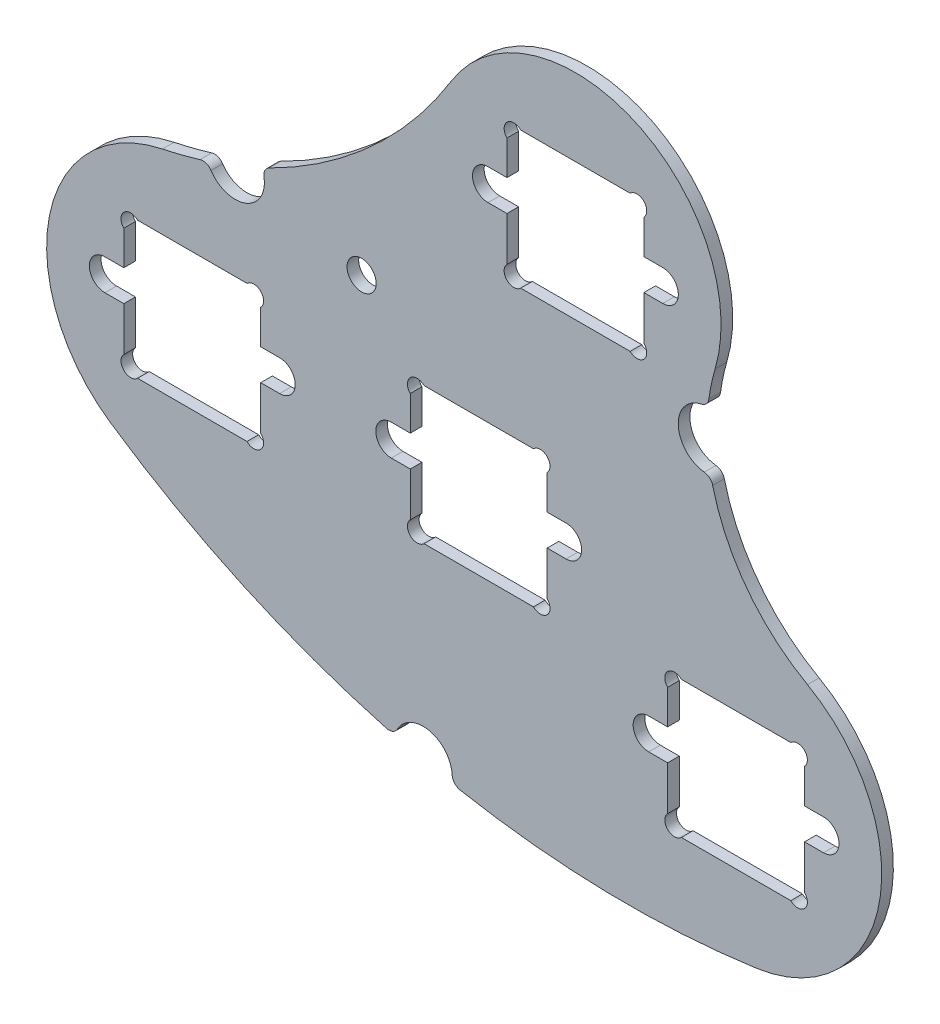
SolidWorks part; units mm, degrees
ref_plane "Front Plane" through (0, 0, 0) normal (0, 0, 1) x (1, 0, 0)
ref_plane "Top Plane" through (0, 0, 0) normal (0, 1, 0) x (1, 0, 0)
ref_plane "Right Plane" through (0, 0, 0) normal (1, 0, 0) x (0, 0, -1)
sketch "Sketch1" plane through (0, 0, 0) normal (0, 0, 1) x (1, 0, 0)
  line L0 (157.8919, 26.2701) -> (191.7747, 29.0915)
  line L1 (157.8919, 26.2701) -> (191.7747, 26.2701)
  line L2 (157.8919, 26.2701) -> (157.8919, 29.0915)
  line L3 (157.8919, 29.0915) -> (191.7747, 29.0915)
  line L4 (191.7747, 26.2701) -> (191.7747, 29.0915)
  line L5 (123.8919, 26.2701) -> (90.0092, 26.2701)
  line L6 (123.8919, 26.2701) -> (123.8919, 29.0915)
  line L7 (123.8919, 29.0915) -> (90.0092, 29.0915)
  line L8 (90.0092, 26.2701) -> (90.0092, 29.0915)
  line L9 (90.0092, 29.0915) -> (123.8919, 26.2701)
  line L10 (168.0919, 58.3601) -> (194.8735, 70.7292)
  line L11 (168.0919, 58.3601) -> (194.8735, 58.3601)
  line L12 (168.0919, 58.3601) -> (168.0919, 70.7292)
  line L13 (168.0919, 70.7292) -> (194.8735, 70.7292)
  line L14 (194.8735, 58.3601) -> (194.8735, 70.7292)
  line L15 (194.8735, 70.7292) -> (224.3587, 70.7292)
  line L16 (194.8735, 70.7292) -> (194.8735, 69.7923)
  line L17 (194.8735, 69.7923) -> (224.3587, 69.7923)
  line L18 (224.3587, 70.7292) -> (224.3587, 69.7923)
  line L19 (224.3587, 69.7923) -> (253.5106, 69.7923)
  line L20 (224.3587, 69.7923) -> (224.3587, 65.2742)
  line L21 (224.3587, 65.2742) -> (253.5106, 65.2742)
  line L22 (253.5106, 69.7923) -> (253.5106, 65.2742)
  line L23 (224.3587, 69.7923) -> (194.8735, 70.7292)
  line L24 (253.5106, 65.2742) -> (224.3587, 69.7923)
  line L25 (170.7502, 87.7401) -> (168.0919, 58.3601)
  line L26 (168.0919, 58.3601) -> (170.7502, 58.3601)
  line L27 (168.0919, 58.3601) -> (168.0919, 87.7401)
  line L28 (168.0919, 87.7401) -> (170.7502, 87.7401)
  line L29 (170.7502, 58.3601) -> (170.7502, 87.7401)
  line L30 (52.9966, 89.4705) -> (24.4119, 82.1791)
  line L31 (24.4119, 82.1791) -> (52.9966, 82.1791)
  line L32 (24.4119, 82.1791) -> (24.4119, 89.4705)
  line L33 (24.4119, 89.4705) -> (52.9966, 89.4705)
  line L34 (52.9966, 82.1791) -> (52.9966, 89.4705)
  line L35 (82.4966, 89.4705) -> (109.0019, 89.4705)
  line L36 (82.4966, 89.4705) -> (82.4966, 76.5201)
  line L37 (82.4966, 76.5201) -> (109.0019, 76.5201)
  line L38 (109.0019, 89.4705) -> (109.0019, 76.5201)
  line L39 (92.4554, 117.2387) -> (82.4966, 117.2387)
  line L40 (92.4554, 117.2387) -> (92.4554, 89.4705)
  line L41 (92.4554, 89.4705) -> (82.4966, 89.4705)
  line L42 (82.4966, 117.2387) -> (82.4966, 89.4705)
  line L43 (92.4554, 117.2387) -> (82.4966, 89.4705)
  line L44 (109.0019, 76.5201) -> (82.4966, 89.4705)
  circle A0 centre (123.8919, 26.2701) radius 14.25
  circle A1 centre (157.8919, 26.2701) radius 14.25
  circle A2 centre (90.0092, 29.0915) radius 14.25
  circle A3 centre (191.7747, 29.0915) radius 14.25
  circle A4 centre (82.4966, 89.4705) radius 11.25
  circle A5 centre (92.4554, 117.2387) radius 11.25
  circle A6 centre (52.9966, 89.4705) radius 11.25
  circle A7 centre (109.0019, 76.5201) radius 11.25
  circle A8 centre (24.4119, 82.1791) radius 11.25
  circle A9 centre (170.7502, 87.7401) radius 11.25
  circle A10 centre (168.0919, 58.3601) radius 11.25
  circle A11 centre (197.5318, 100.1092) radius 11.25
  circle A12 centre (194.8735, 70.7292) radius 11.25
  circle A13 centre (227.0169, 99.1723) radius 11.25
  circle A14 centre (224.3587, 69.7923) radius 11.25
  circle A15 centre (256.1689, 94.6541) radius 11.25
  circle A16 centre (253.5106, 65.2742) radius 11.25
  circle A17 centre (24.4119, 82.1791) radius 12
  circle A18 centre (52.9966, 89.4705) radius 12
  circle A19 centre (92.4554, 117.2387) radius 12
  circle A20 centre (82.4966, 89.4705) radius 12
  circle A21 centre (109.0019, 76.5201) radius 12
  circle A22 centre (168.0919, 58.3601) radius 12
  circle A23 centre (194.8735, 70.7292) radius 12
  circle A24 centre (224.3587, 69.7923) radius 12
  circle A25 centre (253.5106, 65.2742) radius 12
  circle A26 centre (256.1689, 94.6541) radius 12
  circle A27 centre (227.0169, 99.1723) radius 12
  circle A28 centre (197.5318, 100.1092) radius 12
  circle A29 centre (170.7502, 87.7401) radius 12
  circle A30 centre (191.7747, 29.0915) radius 15
  circle A31 centre (157.8919, 26.2701) radius 15
  circle A32 centre (123.8919, 26.2701) radius 15
  circle A33 centre (90.0092, 29.0915) radius 15
  circle A34 centre (173.429, 117.1182) radius 11.25
  circle A35 centre (173.429, 117.1182) radius 12
  dimension "D1" = 28.5
  dimension "D2" = 22.5
  dimension "D3" = 0.75
  dimension "D4" = 0.75
  dimension "D34" = 34
  dimension "D5" = 29.5
  dimension "D6" = 29.5
  dimension "D7" = 29.5
  dimension "D8" = 29.5
  dimension "D9" = 29.5
  dimension "D10" = 29.5
  dimension "D11" = 29.5
  dimension "D12" = 29.5
  dimension "D13" = 29.5
  dimension "D14" = 29.5
  dimension "D15" = 29.5
  dimension "D16" = 29.5
  dimension "D17" = 29.5
  dimension "D18" = 29.5
  dimension "D19" = 34
  dimension "D20" = 34
  dimension "D21" = 32.09
  dimension "D22" = 10.2
  dimension "D23" = 4.76
  dimension "D24" = 4.76
  dimension "D25" = 24.79
  dimension "D26" = 1.82
  dimension "D27" = 8.81
  dimension "D28" = 84.83
  dimension "D29" = 75.69
  dimension "D30" = 70.27
  dimension "D31" = 26.04
  dimension "D32" = 14.89
  dimension "D33" = 50.25
  dimension "D35" = 29.5
  dimension "D36" = 29.5
sketch "Sketch4" plane through (-30.2083, 20.075, 0) normal (0, 0, 1) x (0.9781, -0.2079, 0)
  line L0 (86.1706, 94.1917) -> (105.2206, 75.1417)
  line L1 (67.1206, 94.1917) -> (86.1706, 94.1917)
  line L2 (67.1206, 94.1917) -> (67.1206, 75.1417)
  line L3 (67.1206, 75.1417) -> (86.1706, 75.1417)
  line L4 (86.1706, 94.1917) -> (86.1706, 75.1417)
  line L5 (86.1706, 94.1917) -> (105.2206, 94.1917)
  line L6 (86.1706, 94.1917) -> (86.1706, 75.1417)
  line L7 (86.1706, 75.1417) -> (105.2206, 75.1417)
  line L8 (105.2206, 94.1917) -> (105.2206, 75.1417)
  line L9 (105.2206, 94.1917) -> (124.2706, 94.1917)
  line L10 (105.2206, 94.1917) -> (105.2206, 75.1417)
  line L11 (105.2206, 75.1417) -> (124.2706, 75.1417)
  line L12 (124.2706, 94.1917) -> (124.2706, 75.1417)
  line L13 (86.1706, 94.1917) -> (105.2206, 94.1917)
  line L14 (86.1706, 94.1917) -> (86.1706, 113.2417)
  line L15 (86.1706, 113.2417) -> (105.2206, 113.2417)
  line L16 (105.2206, 94.1917) -> (105.2206, 113.2417)
  line L17 (66.9585, 85.1784) -> (124.4326, 84.1551)
  point P14 (95.6956, 84.6667)
  point P15 (95.6956, 84.6667)
  dimension "D1" = 19.05
sketch "Sketch9" plane through (0, 0, 0) normal (0, 0, 1) x (1, 0, 0)
  line L1 (17.3619, 89.2291) -> (31.4619, 89.2291)
  line L2 (17.3619, 89.2291) -> (17.3619, 75.1291)
  line L3 (17.3619, 75.1291) -> (31.4619, 75.1291)
  line L4 (31.4619, 89.2291) -> (31.4619, 75.1291)
  line L5 (45.9466, 96.5205) -> (60.0466, 96.5205)
  line L6 (45.9466, 96.5205) -> (45.9466, 82.4205)
  line L7 (45.9466, 82.4205) -> (60.0466, 82.4205)
  line L8 (60.0466, 96.5205) -> (60.0466, 82.4205)
  line L9 (75.4466, 96.5205) -> (89.5466, 96.5205)
  line L10 (75.4466, 96.5205) -> (75.4466, 82.4205)
  line L11 (75.4466, 82.4205) -> (89.5466, 82.4205)
  line L12 (89.5466, 96.5205) -> (89.5466, 82.4205)
  line L13 (101.9519, 83.5701) -> (116.0519, 83.5701)
  line L14 (101.9519, 83.5701) -> (101.9519, 69.4701)
  line L15 (101.9519, 69.4701) -> (116.0519, 69.4701)
  line L16 (116.0519, 83.5701) -> (116.0519, 69.4701)
  line L17 (85.4054, 124.2887) -> (99.5054, 124.2887)
  line L18 (85.4054, 124.2887) -> (85.4054, 110.1887)
  line L19 (85.4054, 110.1887) -> (99.5054, 110.1887)
  line L20 (99.5054, 124.2887) -> (99.5054, 110.1887)
  line L21 (82.9592, 36.1415) -> (97.0592, 36.1415)
  line L22 (82.9592, 36.1415) -> (82.9592, 22.0415)
  line L23 (82.9592, 22.0415) -> (97.0592, 22.0415)
  line L24 (97.0592, 36.1415) -> (97.0592, 22.0415)
  line L25 (116.8419, 33.3201) -> (130.9419, 33.3201)
  line L26 (116.8419, 33.3201) -> (116.8419, 19.2201)
  line L27 (116.8419, 19.2201) -> (130.9419, 19.2201)
  line L28 (130.9419, 33.3201) -> (130.9419, 19.2201)
  line L29 (150.8419, 33.3201) -> (164.9419, 33.3201)
  line L30 (150.8419, 33.3201) -> (150.8419, 19.2201)
  line L31 (150.8419, 19.2201) -> (164.9419, 19.2201)
  line L32 (164.9419, 33.3201) -> (164.9419, 19.2201)
  line L33 (184.7247, 36.1415) -> (198.8247, 36.1415)
  line L34 (184.7247, 36.1415) -> (184.7247, 22.0415)
  line L35 (184.7247, 22.0415) -> (198.8247, 22.0415)
  line L36 (198.8247, 36.1415) -> (198.8247, 22.0415)
  line L37 (260.5606, 58.2242) -> (246.4606, 58.2242)
  line L38 (260.5606, 58.2242) -> (260.5606, 72.3242)
  line L39 (260.5606, 72.3242) -> (246.4606, 72.3242)
  line L40 (246.4606, 58.2242) -> (246.4606, 72.3242)
  line L41 (217.3087, 76.8423) -> (231.4087, 76.8423)
  line L42 (217.3087, 76.8423) -> (217.3087, 62.7423)
  line L43 (217.3087, 62.7423) -> (231.4087, 62.7423)
  line L44 (231.4087, 76.8423) -> (231.4087, 62.7423)
  line L45 (187.8235, 77.7792) -> (201.9235, 77.7792)
  line L46 (187.8235, 77.7792) -> (187.8235, 63.6792)
  line L47 (187.8235, 63.6792) -> (201.9235, 63.6792)
  line L48 (201.9235, 77.7792) -> (201.9235, 63.6792)
  line L49 (161.0419, 65.4101) -> (175.1419, 65.4101)
  line L50 (161.0419, 65.4101) -> (161.0419, 51.3101)
  line L51 (161.0419, 51.3101) -> (175.1419, 51.3101)
  line L52 (175.1419, 65.4101) -> (175.1419, 51.3101)
  line L53 (163.7002, 94.7901) -> (177.8002, 94.7901)
  line L54 (163.7002, 94.7901) -> (163.7002, 80.6901)
  line L55 (163.7002, 80.6901) -> (177.8002, 80.6901)
  line L56 (177.8002, 94.7901) -> (177.8002, 80.6901)
  line L57 (190.4818, 107.1592) -> (204.5818, 107.1592)
  line L58 (190.4818, 107.1592) -> (190.4818, 93.0592)
  line L59 (190.4818, 93.0592) -> (204.5818, 93.0592)
  line L60 (204.5818, 107.1592) -> (204.5818, 93.0592)
  line L61 (219.9669, 106.2223) -> (234.0669, 106.2223)
  line L62 (219.9669, 106.2223) -> (219.9669, 92.1223)
  line L63 (219.9669, 92.1223) -> (234.0669, 92.1223)
  line L64 (234.0669, 106.2223) -> (234.0669, 92.1223)
  line L65 (249.1189, 101.7041) -> (263.2189, 101.7041)
  line L66 (249.1189, 101.7041) -> (249.1189, 87.6041)
  line L67 (249.1189, 87.6041) -> (263.2189, 87.6041)
  line L68 (263.2189, 101.7041) -> (263.2189, 87.6041)
  line L69 (166.379, 124.1682) -> (180.479, 124.1682)
  line L70 (166.379, 124.1682) -> (166.379, 110.0682)
  line L71 (166.379, 110.0682) -> (180.479, 110.0682)
  line L72 (180.479, 124.1682) -> (180.479, 110.0682)
  point P72 (24.4119, 89.2291)
  point P74 (52.9966, 96.5205)
  point P76 (82.4966, 96.5205)
  point P78 (92.4554, 124.2887)
  point P80 (109.0019, 83.5701)
  point P82 (90.0092, 36.1415)
  point P84 (123.8919, 33.3201)
  point P86 (157.8919, 33.3201)
  point P88 (191.7747, 36.1415)
  point P90 (168.0919, 65.4101)
  point P92 (170.7502, 94.7901)
  point P94 (173.429, 124.1682)
  point P96 (197.5318, 107.1592)
  point P98 (227.0169, 106.2223)
  point P100 (256.1689, 101.7041)
  point P102 (194.8735, 77.7792)
  point P104 (224.3587, 76.8423)
  point P106 (253.5106, 72.3242)
  point P108 (17.3619, 82.1791)
  point P109 (45.9466, 89.4705)
  point P110 (75.4466, 89.4705)
  point P111 (101.9519, 76.5201)
  point P112 (85.4054, 117.2387)
  point P113 (82.9592, 29.0915)
  point P114 (116.8419, 26.2701)
  point P115 (150.8419, 26.2701)
  point P116 (184.7247, 29.0915)
  point P118 (161.0419, 58.3601)
  point P119 (187.8235, 70.7292)
  point P120 (217.3087, 69.7923)
  point P121 (246.4606, 65.2742)
  point P122 (163.7002, 87.7401)
  point P123 (190.4818, 100.1092)
  point P124 (219.9669, 99.1723)
  point P125 (249.1189, 94.6541)
  point P126 (166.379, 117.1182)
  dimension "D1" = 14.1
sketch "Sketch10" plane through (-22.0981, 19.3454, 0) normal (0, 0, 1) x (0.9781, -0.2079, 0)
  line L1 (61.5108, 90.7441) -> (75.6108, 90.7441)
  line L2 (61.5108, 90.7441) -> (61.5108, 76.6441)
  line L3 (61.5108, 76.6441) -> (75.6108, 76.6441)
  line L4 (75.6108, 90.7441) -> (75.6108, 76.6441)
  line L5 (80.5608, 90.7441) -> (94.6608, 90.7441)
  line L6 (80.5608, 90.7441) -> (80.5608, 76.6441)
  line L7 (80.5608, 76.6441) -> (94.6608, 76.6441)
  line L8 (94.6608, 90.7441) -> (94.6608, 76.6441)
  line L9 (99.6108, 90.7441) -> (113.7108, 90.7441)
  line L10 (99.6108, 90.7441) -> (99.6108, 76.6441)
  line L11 (99.6108, 76.6441) -> (113.7108, 76.6441)
  line L12 (113.7108, 90.7441) -> (113.7108, 76.6441)
  line L13 (80.5608, 109.7941) -> (94.6608, 109.7941)
  line L14 (80.5608, 109.7941) -> (80.5608, 95.6941)
  line L15 (80.5608, 95.6941) -> (94.6608, 95.6941)
  line L16 (94.6608, 109.7941) -> (94.6608, 95.6941)
  line L17 (50.5121, 89.6359) -> (53.4436, 75.8441) construction
  line L18 (59.0358, 93.2191) -> (78.0858, 93.2191) construction
  line L19 (78.0858, 112.2691) -> (97.1358, 112.2691) construction
  line L20 (97.1358, 93.2191) -> (116.1858, 93.2191) construction
  line L21 (78.0858, 93.2191) -> (78.0858, 112.2691) construction
  line L23 (59.0358, 93.2191) -> (59.0358, 74.1691) construction
  point P16 (75.6108, 83.6941)
  point P17 (94.6608, 83.6941)
  point P18 (113.7108, 83.6941)
  point P19 (87.6108, 90.7441)
  point P20 (87.6108, 109.7941)
  point P23 (68.5608, 90.7441)
  point P26 (68.5608, 93.2191)
  point P29 (87.6108, 112.2691)
  point P30 (106.6608, 90.7441)
  point P33 (106.6608, 93.2191)
  point P34 (80.5608, 102.7441)
  point P37 (78.0858, 102.7441)
  point P42 (59.0358, 83.6941)
  point P43 (61.5108, 83.6941)
sketch "Sketch14" plane through (0, 0, 0) normal (0, 0, 1) x (1, 0, 0)
  line L0 (165.1144, 80.6901) -> (163.7002, 82.1043)
  line L1 (163.7002, 93.3758) -> (165.1144, 94.7901)
  line L2 (177.8002, 93.3758) -> (176.386, 94.7901)
  line L3 (179.0648, 110.0682) -> (180.479, 111.4824)
  line L4 (166.379, 111.4824) -> (167.7932, 110.0682)
  line L5 (166.379, 122.754) -> (167.7932, 124.1682)
  line L6 (179.0648, 124.1682) -> (180.479, 122.754)
  line L7 (203.1676, 93.0592) -> (204.5818, 94.4734)
  line L8 (17.3619, 89.2291) -> (17.3619, 75.1291) construction
  line L9 (17.3619, 89.2291) -> (31.4619, 89.2291) construction
  line L10 (17.3619, 87.8149) -> (18.7761, 89.2291)
  line L11 (17.3619, 75.1291) -> (31.4619, 75.1291) construction
  line L12 (31.4619, 89.2291) -> (31.4619, 75.1291) construction
  line L13 (45.9466, 96.5205) -> (60.0466, 96.5205) construction
  line L14 (60.0466, 96.5205) -> (60.0466, 82.4205) construction
  line L15 (45.9466, 96.5205) -> (45.9466, 82.4205) construction
  line L16 (45.9466, 82.4205) -> (60.0466, 82.4205) construction
  line L17 (85.4054, 124.2887) -> (85.4054, 110.1887) construction
  line L18 (85.4054, 124.2887) -> (99.5054, 124.2887) construction
  line L19 (99.5054, 124.2887) -> (99.5054, 110.1887) construction
  line L20 (85.4054, 110.1887) -> (99.5054, 110.1887) construction
  line L21 (101.9519, 83.5701) -> (101.9519, 69.4701) construction
  line L22 (101.9519, 83.5701) -> (116.0519, 83.5701) construction
  line L23 (116.0519, 83.5701) -> (116.0519, 69.4701) construction
  line L24 (101.9519, 69.4701) -> (116.0519, 69.4701) construction
  line L25 (91.2712, 73.6044) -> (105.0631, 70.6729) construction
  line L26 (107.9947, 84.4647) -> (105.0631, 70.6729) construction
  line L27 (94.2028, 87.3963) -> (107.9947, 84.4647) construction
  line L28 (94.2028, 87.3963) -> (91.2712, 73.6044) construction
  line L29 (72.6375, 77.5651) -> (86.4294, 74.6336) construction
  line L30 (89.361, 88.4255) -> (86.4294, 74.6336) construction
  line L31 (75.5691, 91.357) -> (89.361, 88.4255) construction
  line L32 (75.5691, 91.357) -> (72.6375, 77.5651) construction
  line L33 (56.9354, 95.3177) -> (54.0038, 81.5259) construction
  line L34 (56.9354, 95.3177) -> (70.7273, 92.3862) construction
  line L35 (70.7273, 92.3862) -> (67.7957, 78.5943) construction
  line L36 (54.0038, 81.5259) -> (67.7957, 78.5943) construction
  line L37 (76.5983, 96.1988) -> (90.3901, 93.2673) construction
  line L38 (93.3217, 107.0592) -> (90.3901, 93.2673) construction
  line L39 (79.5298, 109.9907) -> (76.5983, 96.1988) construction
  line L40 (79.5298, 109.9907) -> (93.3217, 107.0592) construction
  line L41 (82.9592, 36.1415) -> (82.9592, 22.0415) construction
  line L42 (82.9592, 36.1415) -> (97.0592, 36.1415) construction
  line L43 (82.9592, 22.0415) -> (97.0592, 22.0415) construction
  line L44 (97.0592, 36.1415) -> (97.0592, 22.0415) construction
  line L45 (116.8419, 33.3201) -> (116.8419, 19.2201) construction
  line L46 (116.8419, 33.3201) -> (130.9419, 33.3201) construction
  line L47 (116.8419, 19.2201) -> (130.9419, 19.2201) construction
  line L48 (130.9419, 33.3201) -> (130.9419, 19.2201) construction
  line L49 (150.8419, 33.3201) -> (150.8419, 19.2201) construction
  line L50 (150.8419, 33.3201) -> (164.9419, 33.3201) construction
  line L51 (164.9419, 33.3201) -> (164.9419, 19.2201) construction
  line L52 (150.8419, 19.2201) -> (164.9419, 19.2201) construction
  line L53 (184.7247, 36.1415) -> (184.7247, 22.0415) construction
  line L54 (184.7247, 22.0415) -> (198.8247, 22.0415) construction
  line L55 (198.8247, 36.1415) -> (198.8247, 22.0415) construction
  line L56 (184.7247, 36.1415) -> (198.8247, 36.1415) construction
  line L57 (161.0419, 65.4101) -> (175.1419, 65.4101) construction
  line L58 (175.1419, 65.4101) -> (175.1419, 51.3101) construction
  line L59 (161.0419, 51.3101) -> (175.1419, 51.3101) construction
  line L60 (161.0419, 65.4101) -> (161.0419, 51.3101) construction
  line L61 (187.8235, 77.7792) -> (187.8235, 63.6792) construction
  line L62 (187.8235, 77.7792) -> (201.9235, 77.7792) construction
  line L63 (187.8235, 63.6792) -> (201.9235, 63.6792) construction
  line L64 (201.9235, 77.7792) -> (201.9235, 63.6792) construction
  line L65 (217.3087, 76.8423) -> (217.3087, 62.7423) construction
  line L66 (217.3087, 76.8423) -> (231.4087, 76.8423) construction
  line L67 (231.4087, 76.8423) -> (231.4087, 62.7423) construction
  line L68 (217.3087, 62.7423) -> (231.4087, 62.7423) construction
  line L69 (260.5606, 58.2242) -> (246.4606, 58.2242) construction
  line L70 (260.5606, 58.2242) -> (260.5606, 72.3242) construction
  line L71 (246.4606, 58.2242) -> (246.4606, 72.3242) construction
  line L72 (260.5606, 72.3242) -> (246.4606, 72.3242) construction
  line L73 (249.1189, 101.7041) -> (263.2189, 101.7041) construction
  line L74 (263.2189, 101.7041) -> (263.2189, 87.6041) construction
  line L75 (249.1189, 87.6041) -> (263.2189, 87.6041) construction
  line L76 (249.1189, 101.7041) -> (249.1189, 87.6041) construction
  line L77 (219.9669, 106.2223) -> (219.9669, 92.1223) construction
  line L78 (219.9669, 106.2223) -> (234.0669, 106.2223) construction
  line L79 (234.0669, 106.2223) -> (234.0669, 92.1223) construction
  line L80 (219.9669, 92.1223) -> (234.0669, 92.1223) construction
  line L81 (190.4818, 107.1592) -> (204.5818, 107.1592) construction
  line L82 (204.5818, 107.1592) -> (204.5818, 93.0592) construction
  line L83 (190.4818, 93.0592) -> (204.5818, 93.0592) construction
  line L84 (190.4818, 107.1592) -> (190.4818, 93.0592) construction
  line L85 (163.7002, 94.7901) -> (177.8002, 94.7901) construction
  line L86 (177.8002, 94.7901) -> (177.8002, 80.6901) construction
  line L87 (163.7002, 80.6901) -> (177.8002, 80.6901) construction
  line L88 (163.7002, 94.7901) -> (163.7002, 80.6901) construction
  line L89 (180.479, 124.1682) -> (180.479, 110.0682) construction
  line L90 (166.379, 110.0682) -> (180.479, 110.0682) construction
  line L91 (166.379, 124.1682) -> (166.379, 110.0682) construction
  line L92 (166.379, 124.1682) -> (180.479, 124.1682) construction
  line L93 (17.3619, 76.5433) -> (18.7761, 75.1291)
  line L94 (30.0477, 75.1291) -> (31.4619, 76.5433)
  line L95 (31.4619, 87.8149) -> (30.0477, 89.2291)
  line L96 (45.9466, 95.1063) -> (47.3608, 96.5205)
  line L97 (45.9466, 83.8347) -> (47.3608, 82.4205)
  line L98 (54.2979, 82.9092) -> (55.3871, 81.2318)
  line L99 (58.6323, 82.4205) -> (60.0466, 83.8347)
  line L100 (56.6413, 93.9344) -> (58.3187, 95.0237)
  line L101 (58.6323, 96.5205) -> (60.0466, 95.1063)
  line L102 (69.3439, 92.6802) -> (70.4332, 91.0029)
  line L103 (68.0897, 79.9776) -> (66.4124, 78.8883)
  line L104 (75.2751, 89.9737) -> (76.9524, 91.063)
  line L105 (72.9316, 78.9484) -> (74.0208, 77.2711)
  line L106 (85.0461, 74.9276) -> (86.7234, 76.0169)
  line L107 (89.0669, 87.0421) -> (87.9777, 88.7195)
  line L108 (89.0068, 93.5613) -> (90.6842, 94.6506)
  line L109 (76.8923, 97.5822) -> (77.9816, 95.9048)
  line L110 (91.9384, 107.3532) -> (93.0277, 105.6759)
  line L111 (79.2358, 108.6074) -> (80.9131, 109.6967)
  line L112 (85.4054, 111.6029) -> (86.8196, 110.1887)
  line L113 (98.0912, 110.1887) -> (99.5054, 111.6029)
  line L114 (98.0912, 124.2887) -> (99.5054, 122.8745)
  line L115 (85.4054, 122.8745) -> (86.8196, 124.2887)
  line L116 (93.9088, 86.013) -> (95.5861, 87.1023)
  line L117 (91.5653, 74.9877) -> (92.6546, 73.3104)
  line L118 (103.6798, 70.9669) -> (105.3572, 72.0562)
  line L119 (106.6114, 84.7588) -> (107.7006, 83.0814)
  line L120 (101.9519, 82.1559) -> (103.3662, 83.5701)
  line L121 (101.9519, 70.8843) -> (103.3662, 69.4701)
  line L122 (114.6377, 69.4701) -> (116.0519, 70.8843)
  line L123 (116.0519, 82.1559) -> (114.6377, 83.5701)
  line L124 (82.9592, 34.7272) -> (84.3734, 36.1415)
  line L125 (82.9592, 23.4557) -> (84.3734, 22.0415)
  line L126 (95.645, 22.0415) -> (97.0592, 23.4557)
  line L127 (97.0592, 34.7272) -> (95.645, 36.1415)
  line L128 (116.8419, 31.9059) -> (118.2562, 33.3201)
  line L129 (116.8419, 20.6343) -> (118.2562, 19.2201)
  line L130 (129.5277, 19.2201) -> (130.9419, 20.6343)
  line L131 (130.9419, 31.9059) -> (129.5277, 33.3201)
  line L132 (150.8419, 31.9059) -> (152.2562, 33.3201)
  line L133 (150.8419, 20.6343) -> (152.2562, 19.2201)
  line L134 (163.5277, 19.2201) -> (164.9419, 20.6343)
  line L135 (164.9419, 31.9059) -> (163.5277, 33.3201)
  line L136 (184.7247, 34.7272) -> (186.1389, 36.1415)
  line L137 (184.7247, 23.4557) -> (186.1389, 22.0415)
  line L138 (197.4105, 22.0415) -> (198.8247, 23.4557)
  line L139 (198.8247, 34.7272) -> (197.4105, 36.1415)
  line L140 (173.7277, 51.3101) -> (175.1419, 52.7243)
  line L141 (161.0419, 52.7243) -> (162.4562, 51.3101)
  line L142 (161.0419, 63.9959) -> (162.4562, 65.4101)
  line L143 (173.7277, 65.4101) -> (175.1419, 63.9959)
  line L144 (187.8235, 65.0934) -> (189.2378, 63.6792)
  line L145 (200.5093, 63.6792) -> (201.9235, 65.0934)
  line L146 (200.5093, 77.7792) -> (201.9235, 76.365)
  line L147 (187.8235, 76.365) -> (189.2378, 77.7792)
  line L148 (176.386, 80.6901) -> (177.8002, 82.1043)
  line L149 (204.5818, 105.745) -> (203.1676, 107.1592)
  line L150 (191.896, 107.1592) -> (190.4818, 105.745)
  line L151 (190.4818, 94.4734) -> (191.896, 93.0592)
  line L152 (219.9669, 104.8081) -> (221.3812, 106.2223)
  line L153 (232.6527, 106.2223) -> (234.0669, 104.8081)
  line L154 (234.0669, 93.5365) -> (232.6527, 92.1223)
  line L155 (219.9669, 93.5365) -> (221.3812, 92.1223)
  line L156 (229.9944, 76.8423) -> (231.4087, 75.4281)
  line L157 (217.3087, 75.4281) -> (218.7229, 76.8423)
  line L158 (217.3087, 64.1565) -> (218.7229, 62.7423)
  line L159 (229.9944, 62.7423) -> (231.4087, 64.1565)
  line L160 (259.1464, 72.3242) -> (260.5606, 70.9099)
  line L161 (246.4606, 70.9099) -> (247.8748, 72.3242)
  line L162 (259.1464, 58.2242) -> (260.5606, 59.6384)
  line L163 (247.8748, 58.2242) -> (246.4606, 59.6384)
  line L164 (261.8047, 87.6041) -> (263.2189, 89.0183)
  line L165 (249.1189, 89.0183) -> (250.5331, 87.6041)
  line L166 (249.1189, 100.2899) -> (250.5331, 101.7041)
  line L167 (261.8047, 101.7041) -> (263.2189, 100.2899)
  line L168 (75.4466, 96.5205) -> (75.4466, 82.4205) construction
  line L169 (75.4466, 96.5205) -> (89.5466, 96.5205) construction
  line L170 (89.5466, 96.5205) -> (89.5466, 82.4205) construction
  line L171 (75.4466, 82.4205) -> (89.5466, 82.4205) construction
  line L172 (76.8608, 96.5205) -> (75.4466, 95.1063)
  line L173 (88.1323, 96.5205) -> (89.5466, 95.1063)
  line L174 (89.5466, 83.8347) -> (88.1323, 82.4205)
  line L175 (75.4466, 83.8347) -> (76.8608, 82.4205)
  arc A0 (17.3619, 87.8149) -> (18.7761, 89.2291) centre (18.069, 88.522) cw
  arc A1 (18.7761, 75.1291) -> (17.3619, 76.5433) centre (18.069, 75.8362) cw
  arc A2 (31.4619, 76.5433) -> (30.0477, 75.1291) centre (30.7548, 75.8362) cw
  arc A3 (30.0477, 89.2291) -> (31.4619, 87.8149) centre (30.7548, 88.522) cw
  arc A4 (58.6323, 96.5205) -> (60.0466, 95.1063) centre (59.3394, 95.8134) cw
  arc A5 (45.9466, 95.1063) -> (47.3608, 96.5205) centre (46.6537, 95.8134) cw
  arc A6 (47.3608, 82.4205) -> (45.9466, 83.8347) centre (46.6537, 83.1276) cw
  arc A7 (60.0466, 83.8347) -> (58.6323, 82.4205) centre (59.3394, 83.1276) cw
  arc A8 (85.4054, 122.8745) -> (86.8196, 124.2887) centre (86.1125, 123.5816) cw
  arc A9 (98.0912, 124.2887) -> (99.5054, 122.8745) centre (98.7983, 123.5816) cw
  arc A10 (99.5054, 111.6029) -> (98.0912, 110.1887) centre (98.7983, 110.8958) cw
  arc A11 (85.4054, 111.6029) -> (86.8196, 110.1887) centre (86.1125, 110.8958) ccw
  arc A12 (101.9519, 82.1559) -> (103.3662, 83.5701) centre (102.6591, 82.863) cw
  arc A13 (114.6377, 83.5701) -> (116.0519, 82.1559) centre (115.3448, 82.863) cw
  arc A14 (116.0519, 70.8843) -> (114.6377, 69.4701) centre (115.3448, 70.1772) cw
  arc A15 (101.9519, 70.8843) -> (103.3662, 69.4701) centre (102.6591, 70.1772) ccw
  arc A16 (103.6798, 70.9669) -> (105.3572, 72.0562) centre (104.5185, 71.5115) ccw
  arc A17 (106.6114, 84.7588) -> (107.7006, 83.0814) centre (107.156, 83.9201) cw
  arc A18 (93.9088, 86.013) -> (95.5861, 87.1023) centre (94.7474, 86.5576) cw
  arc A19 (91.5653, 74.9877) -> (92.6546, 73.3104) centre (92.1099, 74.1491) ccw
  arc A20 (85.0461, 74.9276) -> (86.7234, 76.0169) centre (85.8848, 75.4722) ccw
  arc A21 (87.9777, 88.7195) -> (89.0669, 87.0421) centre (88.5223, 87.8808) cw
  arc A22 (75.2751, 89.9737) -> (76.9524, 91.063) centre (76.1137, 90.5183) cw
  arc A23 (72.9316, 78.9484) -> (74.0208, 77.2711) centre (73.4762, 78.1098) ccw
  arc A24 (56.6413, 93.9344) -> (58.3187, 95.0237) centre (57.48, 94.4791) cw
  arc A25 (69.3439, 92.6802) -> (70.4332, 91.0029) centre (69.8886, 91.8415) cw
  arc A26 (68.0897, 79.9776) -> (66.4124, 78.8883) centre (67.2511, 79.433) cw
  arc A27 (54.2979, 82.9092) -> (55.3871, 81.2318) centre (54.8425, 82.0705) ccw
  arc A28 (89.0068, 93.5613) -> (90.6842, 94.6506) centre (89.8455, 94.106) ccw
  arc A29 (76.8923, 97.5822) -> (77.9816, 95.9048) centre (77.4369, 96.7435) ccw
  arc A30 (79.2358, 108.6074) -> (80.9131, 109.6967) centre (80.0744, 109.1521) cw
  arc A31 (91.9384, 107.3532) -> (93.0277, 105.6759) centre (92.483, 106.5145) cw
  arc A32 (82.9592, 34.7272) -> (84.3734, 36.1415) centre (83.6663, 35.4344) cw
  arc A33 (82.9592, 23.4557) -> (84.3734, 22.0415) centre (83.6663, 22.7486) ccw
  arc A34 (95.645, 22.0415) -> (97.0592, 23.4557) centre (96.3521, 22.7486) ccw
  arc A35 (95.645, 36.1415) -> (97.0592, 34.7272) centre (96.3521, 35.4344) cw
  arc A36 (116.8419, 31.9059) -> (118.2562, 33.3201) centre (117.5491, 32.613) cw
  arc A37 (116.8419, 20.6343) -> (118.2562, 19.2201) centre (117.5491, 19.9272) ccw
  arc A38 (129.5277, 19.2201) -> (130.9419, 20.6343) centre (130.2348, 19.9272) ccw
  arc A39 (129.5277, 33.3201) -> (130.9419, 31.9059) centre (130.2348, 32.613) cw
  arc A40 (150.8419, 31.9059) -> (152.2562, 33.3201) centre (151.5491, 32.613) cw
  arc A41 (163.5277, 33.3201) -> (164.9419, 31.9059) centre (164.2348, 32.613) cw
  arc A42 (164.9419, 20.6343) -> (163.5277, 19.2201) centre (164.2348, 19.9272) cw
  arc A43 (150.8419, 20.6343) -> (152.2562, 19.2201) centre (151.5491, 19.9272) ccw
  arc A44 (184.7247, 23.4557) -> (186.1389, 22.0415) centre (185.4318, 22.7486) ccw
  arc A45 (197.4105, 22.0415) -> (198.8247, 23.4557) centre (198.1176, 22.7486) ccw
  arc A46 (197.4105, 36.1415) -> (198.8247, 34.7272) centre (198.1176, 35.4344) cw
  arc A47 (184.7247, 34.7272) -> (186.1389, 36.1415) centre (185.4318, 35.4344) cw
  arc A48 (173.7277, 65.4101) -> (175.1419, 63.9959) centre (174.4348, 64.703) cw
  arc A49 (175.1419, 52.7243) -> (173.7277, 51.3101) centre (174.4348, 52.0172) cw
  arc A50 (161.0419, 52.7243) -> (162.4562, 51.3101) centre (161.7491, 52.0172) ccw
  arc A51 (161.0419, 63.9959) -> (162.4562, 65.4101) centre (161.7491, 64.703) cw
  arc A52 (187.8235, 76.365) -> (189.2378, 77.7792) centre (188.5306, 77.0721) cw
  arc A53 (187.8235, 65.0934) -> (189.2378, 63.6792) centre (188.5306, 64.3863) ccw
  arc A54 (200.5093, 63.6792) -> (201.9235, 65.0934) centre (201.2164, 64.3863) ccw
  arc A55 (200.5093, 77.7792) -> (201.9235, 76.365) centre (201.2164, 77.0721) cw
  arc A56 (217.3087, 75.4281) -> (218.7229, 76.8423) centre (218.0158, 76.1352) cw
  arc A57 (229.9944, 76.8423) -> (231.4087, 75.4281) centre (230.7016, 76.1352) cw
  arc A58 (231.4087, 64.1565) -> (229.9944, 62.7423) centre (230.7016, 63.4494) cw
  arc A59 (217.3087, 64.1565) -> (218.7229, 62.7423) centre (218.0158, 63.4494) ccw
  arc A60 (259.1464, 58.2242) -> (260.5606, 59.6384) centre (259.8535, 58.9313) ccw
  arc A61 (246.4606, 59.6384) -> (247.8748, 58.2242) centre (247.1677, 58.9313) ccw
  arc A62 (246.4606, 70.9099) -> (247.8748, 72.3242) centre (247.1677, 71.617) cw
  arc A63 (259.1464, 72.3242) -> (260.5606, 70.9099) centre (259.8535, 71.617) cw
  arc A64 (261.8047, 101.7041) -> (263.2189, 100.2899) centre (262.5118, 100.997) cw
  arc A65 (263.2189, 89.0183) -> (261.8047, 87.6041) centre (262.5118, 88.3112) cw
  arc A66 (250.5331, 87.6041) -> (249.1189, 89.0183) centre (249.826, 88.3112) cw
  arc A67 (249.1189, 100.2899) -> (250.5331, 101.7041) centre (249.826, 100.997) cw
  arc A68 (219.9669, 104.8081) -> (221.3812, 106.2223) centre (220.674, 105.5152) cw
  arc A69 (232.6527, 106.2223) -> (234.0669, 104.8081) centre (233.3598, 105.5152) cw
  arc A70 (234.0669, 93.5365) -> (232.6527, 92.1223) centre (233.3598, 92.8294) cw
  arc A71 (221.3812, 92.1223) -> (219.9669, 93.5365) centre (220.674, 92.8294) cw
  arc A72 (203.1676, 107.1592) -> (204.5818, 105.745) centre (203.8747, 106.4521) cw
  arc A73 (204.5818, 94.4734) -> (203.1676, 93.0592) centre (203.8747, 93.7663) cw
  arc A74 (191.896, 93.0592) -> (190.4818, 94.4734) centre (191.1889, 93.7663) cw
  arc A75 (190.4818, 105.745) -> (191.896, 107.1592) centre (191.1889, 106.4521) cw
  arc A76 (176.386, 94.7901) -> (177.8002, 93.3758) centre (177.0931, 94.0829) cw
  arc A77 (177.8002, 82.1043) -> (176.386, 80.6901) centre (177.0931, 81.3972) cw
  arc A78 (165.1144, 80.6901) -> (163.7002, 82.1043) centre (164.4073, 81.3972) cw
  arc A79 (163.7002, 93.3758) -> (165.1144, 94.7901) centre (164.4073, 94.0829) cw
  arc A80 (180.479, 111.4824) -> (179.0648, 110.0682) centre (179.7719, 110.7753) cw
  arc A81 (167.7932, 110.0682) -> (166.379, 111.4824) centre (167.0861, 110.7753) cw
  arc A82 (179.0648, 124.1682) -> (180.479, 122.754) centre (179.7719, 123.4611) cw
  arc A83 (166.379, 122.754) -> (167.7932, 124.1682) centre (167.0861, 123.4611) cw
  arc A84 (75.4466, 95.1063) -> (76.8608, 96.5205) centre (76.1537, 95.8134) cw
  arc A85 (88.1323, 96.5205) -> (89.5466, 95.1063) centre (88.8394, 95.8134) cw
  arc A86 (89.5466, 83.8347) -> (88.1323, 82.4205) centre (88.8394, 83.1276) cw
  arc A87 (76.8608, 82.4205) -> (75.4466, 83.8347) centre (76.1537, 83.1276) cw
  dimension "D1" = 45
  dimension "D2" = 1
  dimension "D71" = 45
  dimension "D3" = 45
  dimension "D4" = 45
  dimension "D5" = 45
  dimension "D6" = 45
  dimension "D7" = 45
  dimension "D8" = 45
  dimension "D9" = 45
  dimension "D10" = 45
  dimension "D11" = 45
  dimension "D12" = 45
  dimension "D13" = 45
  dimension "D14" = 45
  dimension "D15" = 45
  dimension "D16" = 45
  dimension "D17" = 45
  dimension "D18" = 45
  dimension "D19" = 45
  dimension "D20" = 45
  dimension "D21" = 45
  dimension "D22" = 45
  dimension "D23" = 45
  dimension "D24" = 45
  dimension "D25" = 45
  dimension "D26" = 45
  dimension "D27" = 45
  dimension "D28" = 45
  dimension "D29" = 45
  dimension "D30" = 45
  dimension "D31" = 45
  dimension "D32" = 45
  dimension "D33" = 45
  dimension "D34" = 45
  dimension "D35" = 45
  dimension "D36" = 45
  dimension "D37" = 45
  dimension "D38" = 45
  dimension "D39" = 45
  dimension "D40" = 45
  dimension "D41" = 45
  dimension "D42" = 45
  dimension "D43" = 45
  dimension "D44" = 45
  dimension "D45" = 45
  dimension "D46" = 45
  dimension "D47" = 45
  dimension "D48" = 45
  dimension "D49" = 45
  dimension "D50" = 45
  dimension "D51" = 45
  dimension "D52" = 45
  dimension "D53" = 45
  dimension "D54" = 45
  dimension "D55" = 45
  dimension "D56" = 45
  dimension "D57" = 45
  dimension "D58" = 45
  dimension "D59" = 45
  dimension "D60" = 45
  dimension "D61" = 45
  dimension "D62" = 45
  dimension "D63" = 45
  dimension "D64" = 45
  dimension "D65" = 45
  dimension "D66" = 45
  dimension "D67" = 45
  dimension "D68" = 45
  dimension "D69" = 45
  dimension "D70" = 45
  dimension "D72" = 45
  dimension "D73" = 45
  dimension "D74" = 45
  dimension "D75" = 45
  dimension "D76" = 45
  dimension "D77" = 45
  dimension "D78" = 45
  dimension "D79" = 45
  dimension "D80" = 45
  dimension "D81" = 45
  dimension "D82" = 45
  dimension "D83" = 45
  dimension "D84" = 45
  dimension "D85" = 45
  dimension "D86" = 45
  dimension "D87" = 45
  dimension "D88" = 45
  dimension "D89" = 45
sketch "Sketch16" plane through (0, 0, 0) normal (0, 0, 1) x (1, 0, 0)
  line L0 (81.0092, 30.6915) -> (99.0092, 30.6915)
  line L5 (17.3619, 89.2291) -> (17.3619, 75.1291) construction
  line L6 (81.0092, 30.6915) -> (81.0092, 27.4915)
  line L7 (17.3619, 75.1291) -> (31.4619, 75.1291) construction
  line L8 (15.4119, 83.7791) -> (33.4119, 83.7791)
  line L9 (15.4119, 83.7791) -> (15.4119, 80.5791)
  line L10 (15.4119, 80.5791) -> (33.4119, 80.5791)
  line L11 (33.4119, 83.7791) -> (33.4119, 80.5791)
  line L12 (81.0092, 27.4915) -> (99.0092, 27.4915)
  line L13 (99.0092, 30.6915) -> (99.0092, 27.4915)
  line L14 (114.8919, 27.8701) -> (132.8919, 27.8701)
  line L15 (114.8919, 27.8701) -> (114.8919, 24.6701)
  line L16 (114.8919, 24.6701) -> (132.8919, 24.6701)
  line L17 (132.8919, 27.8701) -> (132.8919, 24.6701)
  line L18 (148.8919, 27.8701) -> (166.8919, 27.8701)
  line L19 (148.8919, 27.8701) -> (148.8919, 24.6701)
  line L20 (148.8919, 24.6701) -> (166.8919, 24.6701)
  line L21 (166.8919, 27.8701) -> (166.8919, 24.6701)
  line L22 (182.7747, 30.6915) -> (200.7747, 30.6915)
  line L23 (182.7747, 30.6915) -> (182.7747, 27.4915)
  line L24 (182.7747, 27.4915) -> (200.7747, 27.4915)
  line L25 (200.7747, 30.6915) -> (200.7747, 27.4915)
  line L26 (43.9966, 91.5705) -> (61.9966, 91.5705)
  line L27 (43.9966, 91.5705) -> (43.9966, 88.3705)
  line L28 (43.9966, 88.3705) -> (61.9966, 88.3705)
  line L29 (61.9966, 91.5705) -> (61.9966, 88.3705)
  line L30 (73.4966, 91.5705) -> (91.4966, 91.5705)
  line L31 (73.4966, 91.5705) -> (73.4966, 88.3705)
  line L32 (73.4966, 88.3705) -> (91.4966, 88.3705)
  line L33 (91.4966, 91.5705) -> (91.4966, 88.3705)
  line L34 (100.0019, 78.6201) -> (118.0019, 78.6201)
  line L35 (100.0019, 78.6201) -> (100.0019, 75.4201)
  line L36 (100.0019, 75.4201) -> (118.0019, 75.4201)
  line L37 (118.0019, 78.6201) -> (118.0019, 75.4201)
  line L38 (83.4554, 119.3387) -> (101.4554, 119.3387)
  line L39 (83.4554, 119.3387) -> (83.4554, 116.1387)
  line L40 (83.4554, 116.1387) -> (101.4554, 116.1387)
  line L41 (101.4554, 119.3387) -> (101.4554, 116.1387)
  line L42 (164.429, 118.7182) -> (182.429, 118.7182)
  line L43 (164.429, 118.7182) -> (164.429, 115.5182)
  line L44 (164.429, 115.5182) -> (182.429, 115.5182)
  line L45 (182.429, 118.7182) -> (182.429, 115.5182)
  line L46 (161.7502, 89.3401) -> (179.7502, 89.3401)
  line L47 (161.7502, 89.3401) -> (161.7502, 86.1401)
  line L48 (161.7502, 86.1401) -> (179.7502, 86.1401)
  line L49 (179.7502, 89.3401) -> (179.7502, 86.1401)
  line L50 (188.5318, 101.7092) -> (206.5318, 101.7092)
  line L51 (188.5318, 101.7092) -> (188.5318, 98.5092)
  line L52 (188.5318, 98.5092) -> (206.5318, 98.5092)
  line L53 (206.5318, 101.7092) -> (206.5318, 98.5092)
  line L54 (159.0919, 59.9601) -> (177.0919, 59.9601)
  line L55 (159.0919, 59.9601) -> (159.0919, 56.7601)
  line L56 (159.0919, 56.7601) -> (177.0919, 56.7601)
  line L57 (177.0919, 59.9601) -> (177.0919, 56.7601)
  line L58 (185.8735, 72.3292) -> (203.8735, 72.3292)
  line L59 (185.8735, 72.3292) -> (185.8735, 69.1292)
  line L60 (185.8735, 69.1292) -> (203.8735, 69.1292)
  line L61 (203.8735, 72.3292) -> (203.8735, 69.1292)
  line L62 (218.0169, 100.7723) -> (236.0169, 100.7723)
  line L63 (218.0169, 100.7723) -> (218.0169, 97.5723)
  line L64 (218.0169, 97.5723) -> (236.0169, 97.5723)
  line L65 (236.0169, 100.7723) -> (236.0169, 97.5723)
  line L66 (215.3587, 71.3923) -> (233.3587, 71.3923)
  line L67 (215.3587, 71.3923) -> (215.3587, 68.1923)
  line L68 (215.3587, 68.1923) -> (233.3587, 68.1923)
  line L69 (233.3587, 71.3923) -> (233.3587, 68.1923)
  line L70 (247.1689, 96.2541) -> (265.1689, 96.2541)
  line L71 (247.1689, 96.2541) -> (247.1689, 93.0541)
  line L72 (247.1689, 93.0541) -> (265.1689, 93.0541)
  line L73 (265.1689, 96.2541) -> (265.1689, 93.0541)
  line L74 (244.5106, 66.8742) -> (262.5106, 66.8742)
  line L75 (244.5106, 66.8742) -> (244.5106, 63.6742)
  line L76 (244.5106, 63.6742) -> (262.5106, 63.6742)
  line L77 (262.5106, 66.8742) -> (262.5106, 63.6742)
  circle A0 centre (15.4119, 82.1791) radius 1.6
  circle A1 centre (33.4119, 82.1791) radius 1.6
  circle A2 centre (81.0092, 29.0915) radius 1.6
  circle A3 centre (99.0092, 29.0915) radius 1.6
  circle A4 centre (114.8919, 26.2701) radius 1.6
  circle A5 centre (132.8919, 26.2701) radius 1.6
  circle A6 centre (148.8919, 26.2701) radius 1.6
  circle A7 centre (166.8919, 26.2701) radius 1.6
  circle A8 centre (182.7747, 29.0915) radius 1.6
  circle A9 centre (200.7747, 29.0915) radius 1.6
  circle A10 centre (43.9966, 89.9705) radius 1.6
  circle A11 centre (61.9966, 89.9705) radius 1.6
  circle A12 centre (73.4966, 89.9705) radius 1.6
  circle A13 centre (91.4966, 89.9705) radius 1.6
  circle A14 centre (100.0019, 77.0201) radius 1.6
  circle A15 centre (118.0019, 77.0201) radius 1.6
  circle A16 centre (83.4554, 117.7387) radius 1.6
  circle A17 centre (101.4554, 117.7387) radius 1.6
  circle A18 centre (164.429, 117.1182) radius 1.6
  circle A19 centre (182.429, 117.1182) radius 1.6
  circle A20 centre (161.7502, 87.7401) radius 1.6
  circle A21 centre (179.7502, 87.7401) radius 1.6
  circle A22 centre (188.5318, 100.1092) radius 1.6
  circle A23 centre (206.5318, 100.1092) radius 1.6
  circle A24 centre (159.0919, 58.3601) radius 1.6
  circle A25 centre (177.0919, 58.3601) radius 1.6
  circle A26 centre (185.8735, 70.7292) radius 1.6
  circle A27 centre (203.8735, 70.7292) radius 1.6
  circle A28 centre (218.0169, 99.1723) radius 1.6
  circle A29 centre (236.0169, 99.1723) radius 1.6
  circle A30 centre (215.3587, 69.7923) radius 1.6
  circle A31 centre (233.3587, 69.7923) radius 1.6
  circle A32 centre (247.1689, 94.6541) radius 1.6
  circle A33 centre (265.1689, 94.6541) radius 1.6
  circle A34 centre (244.5106, 65.2742) radius 1.6
  circle A35 centre (262.5106, 65.2742) radius 1.6
  point P2 (24.4119, 75.1291)
  point P6 (17.3619, 82.1791)
  point P14 (24.4119, 80.5791)
  point P53 (90.0092, 30.6915)
  point P57 (123.8919, 27.8701)
  point P60 (157.8919, 27.8701)
  point P63 (191.7747, 30.6915)
  point P73 (52.9966, 91.5705)
  point P83 (82.4966, 91.5705)
  point P93 (109.0019, 78.6201)
  point P103 (92.4554, 119.3387)
  point P113 (173.429, 118.7182)
  point P123 (170.7502, 89.3401)
  point P133 (197.5318, 101.7092)
  point P143 (168.0919, 59.9601)
  point P153 (194.8735, 72.3292)
  point P163 (227.0169, 100.7723)
  point P173 (224.3587, 71.3923)
  point P183 (256.1689, 96.2541)
  point P193 (253.5106, 66.8742)
  dimension "D1" = 3.2
  dimension "D2" = 18
  dimension "D3" = 0.5
  dimension "D4" = 0.5
  dimension "D5" = 0.5
  dimension "D6" = 0.5
sketch "Sketch8" plane through (0, 0, 0) normal (0, 0, 1) x (1, 0, 0)
  line L0 (52.2844, 74.6389) -> (82.4966, 89.4705)
  line L1 (86.9403, 110.9459) -> (79.0189, 73.6784)
  line L2 (77.6235, 112.9262) -> (96.2572, 108.9655) construction
  line L3 (69.702, 75.6588) -> (88.3357, 71.6981) construction
  line L4 (53.3861, 72.3947) -> (55.5425, 73.4534)
  line L5 (99.6829, 63.2465) -> (101.1557, 61.3487)
  line L6 (103.1308, 62.8814) -> (82.4966, 89.4705)
  line L8 (73.6628, 94.2925) -> (77.6235, 112.9262) construction
  line L9 (55.029, 98.2532) -> (73.6628, 94.2925) construction
  line L13 (93.9017, 130.158) -> (94.0202, 130.4883)
  line L14 (99.5495, 128.1325) -> (99.6679, 128.4628)
  line L16 (99.4417, 62.7418) -> (100.7607, 61.0421)
  line L17 (55.5377, 72.894) -> (53.6064, 71.9459)
  line L19 (82.4966, 89.4705) -> (96.8441, 129.4755)
  circle A1 centre (57.4203, 106.4022) radius 2.5
  circle A2 centre (106.0456, 106.2134) radius 2.5
  circle A3 centre (76.7673, 63.0854) radius 2.5
  circle A4 centre (52.9966, 89.4705) radius 13
  circle A6 centre (92.4554, 117.2387) radius 13
  circle A7 centre (109.0019, 76.5201) radius 13
  circle A8 centre (82.4966, 89.4705) radius 25
  arc A10 (50.3337, 102.1949) -> (81.377, 124.0408) centre (40.5107, 149.1329) ccw
  circle A11 centre (103.1308, 62.8814) radius 2.5
  circle A12 centre (52.2844, 74.6389) radius 2.5
  circle A13 centre (96.8441, 129.4755) radius 2.5
  circle A14 centre (52.2844, 74.6389) radius 3
  circle A15 centre (103.1308, 62.8814) radius 3
  circle A16 centre (96.8441, 129.4755) radius 3
  arc A17 (104.9258, 113.5659) -> (115.3756, 87.8504) centre (126.3001, 107.2707) ccw
  arc A18 (45.7038, 78.7088) -> (110.8301, 63.6492) centre (97.7768, 155.5511) ccw
  circle A19 centre (92.4554, 117.2387) radius 15
  circle A20 centre (109.0019, 76.5201) radius 15
  circle A21 centre (52.9966, 89.4705) radius 15
  circle A22 centre (82.4966, 89.4705) radius 27
  arc A23 (44.5818, 77.0531) -> (111.1113, 61.6691) centre (97.7768, 155.5511) ccw
  arc A24 (49.924, 104.1525) -> (79.6727, 125.0873) centre (40.5107, 149.1329) ccw
  arc A25 (106.8443, 113.0008) -> (116.3562, 89.5935) centre (126.3001, 107.2707) ccw
  circle A26 centre (52.9966, 89.4705) radius 12.5
  circle A27 centre (109.0019, 76.5201) radius 12.5
  circle A28 centre (92.4554, 117.2387) radius 12.5
  circle A29 centre (82.4966, 89.4705) radius 24.5
  arc A30 (104.4462, 113.7071) -> (115.1305, 87.4146) centre (126.3001, 107.2707) ccw
  arc A31 (110.7597, 64.1443) -> (45.9842, 79.1227) centre (97.7768, 155.5511) cw
  arc A32 (50.4361, 101.7055) -> (81.8031, 123.7792) centre (40.5107, 149.1329) ccw
  circle A33 centre (52.9966, 89.4705) radius 15.5
  circle A34 centre (109.0019, 76.5201) radius 15.5
  circle A35 centre (92.4554, 117.2387) radius 15.5
  circle A36 centre (82.4966, 89.4705) radius 27.5
  arc A37 (107.3239, 112.8596) -> (116.6013, 90.0293) centre (126.3001, 107.2707) ccw
  arc A38 (111.1816, 61.1741) -> (44.3013, 76.6392) centre (97.7768, 155.5511) cw
  arc A39 (49.8216, 104.6419) -> (79.2466, 125.349) centre (40.5107, 149.1329) ccw
  circle A40 centre (106.0456, 106.2134) radius 3
  circle A41 centre (76.7673, 63.0854) radius 3
  circle A42 centre (57.4203, 106.4022) radius 3
  circle A43 centre (70.4353, 103.1572) radius 2.5
  dimension "D3" = 26
  dimension "D4" = 5
  dimension "D7" = 6
  dimension "D8" = 50
  dimension "D1" = 2
  dimension "D2" = 2
  dimension "D5" = 0.5
  dimension "D6" = 0.5
  dimension "D9" = 0.5
  dimension "D10" = 0.5
  dimension "D11" = 5
  dimension "D12" = 8
sketch "Sketch2" plane through (0, 0, 0) normal (0, 0, 1) x (1, 0, 0)
  line L0 (30.4119, 134.2387) -> (8.4119, 112.2387)
  line L1 (16.4119, 134.2387) -> (264.1689, 134.2387)
  line L2 (8.4119, 126.2387) -> (8.4119, 15.2864)
  line L3 (16.4119, 7.2864) -> (264.1689, 7.2864)
  line L4 (272.1689, 126.2387) -> (272.1689, 15.2864)
  line L5 (16.4119, 136.2387) -> (264.1689, 136.2387)
  line L6 (6.4119, 126.2387) -> (6.4119, 15.2864)
  line L7 (16.4119, 5.2864) -> (264.1689, 5.2864)
  line L8 (274.1689, 126.2387) -> (274.1689, 15.2864)
  line L9 (250.1689, 134.2387) -> (272.1689, 112.2387)
  line L10 (6.4119, 110.2387) -> (32.4119, 136.2387)
  line L11 (248.1689, 136.2387) -> (274.1689, 110.2387)
  line L12 (6.4119, 107.4103) -> (35.2403, 136.2387)
  line L13 (245.3405, 136.2387) -> (274.1689, 107.4103)
  circle A0 centre (24.4119, 82.1791) radius 12 construction
  circle A2 centre (256.1689, 94.6541) radius 12 construction
  arc A3 (264.1689, 136.2387) -> (274.1689, 126.2387) centre (264.1689, 126.2387) cw
  circle A4 centre (123.8919, 26.2701) radius 15 construction
  arc A5 (264.1689, 5.2864) -> (274.1689, 15.2864) centre (264.1689, 15.2864) ccw
  arc A6 (6.4119, 15.2864) -> (16.4119, 5.2864) centre (16.4119, 15.2864) ccw
  arc A7 (16.4119, 136.2387) -> (6.4119, 126.2387) centre (16.4119, 126.2387) ccw
  arc A8 (264.1689, 134.2387) -> (272.1689, 126.2387) centre (264.1689, 126.2387) cw
  arc A9 (264.1689, 7.2864) -> (272.1689, 15.2864) centre (264.1689, 15.2864) ccw
  arc A10 (8.4119, 15.2864) -> (16.4119, 7.2864) centre (16.4119, 15.2864) ccw
  arc A11 (16.4119, 134.2387) -> (8.4119, 126.2387) centre (16.4119, 126.2387) ccw
  circle A12 centre (92.4554, 117.2387) radius 13 construction
  point P4 (12.4119, 82.1791)
  point P5 (92.4554, 130.2387)
  point P8 (268.1689, 94.6541)
  point P14 (124.5912, 11.2864)
  point P36 (30.4119, 134.2387)
  point P39 (250.1689, 134.2387)
  dimension "D9" = 10
  dimension "D10" = 8
  dimension "D1" = 4
  dimension "D2" = 4
  dimension "D3" = 4
  dimension "D4" = 4
  dimension "D5" = 2
  dimension "D6" = 2
  dimension "D7" = 2
  dimension "D8" = 2
  dimension "D11" = 14
  dimension "D12" = 45
  dimension "D13" = 14
  dimension "D14" = 45
  dimension "D15" = 2
  dimension "D16" = 2
sketch "Sketch6" plane through (0, 0, 0) normal (0, 0, 1) x (1, 0, 0)
  line L0 (44.9119, 130.2387) -> (56.9119, 130.2387)
  line L1 (31.4119, 130.2387) -> (43.4119, 130.2387)
  line L2 (31.4119, 130.2387) -> (31.4119, 118.2387)
  line L3 (31.4119, 118.2387) -> (43.4119, 118.2387)
  line L4 (43.4119, 130.2387) -> (43.4119, 118.2387)
  line L5 (34.1619, 133.2387) -> (40.6619, 133.2387)
  line L6 (34.1619, 133.2387) -> (34.1619, 115.2387)
  line L7 (34.1619, 115.2387) -> (40.6619, 115.2387)
  line L8 (40.6619, 133.2387) -> (40.6619, 115.2387)
  line L9 (44.9119, 130.2387) -> (44.9119, 118.2387)
  line L10 (44.9119, 118.2387) -> (56.9119, 118.2387)
  line L11 (56.9119, 130.2387) -> (56.9119, 118.2387)
  line L12 (47.6619, 133.2387) -> (54.1619, 133.2387)
  line L13 (47.6619, 133.2387) -> (47.6619, 115.2387)
  line L14 (47.6619, 115.2387) -> (54.1619, 115.2387)
  line L15 (54.1619, 133.2387) -> (54.1619, 115.2387)
  line L16 (58.4119, 130.2387) -> (70.4119, 130.2387)
  line L17 (58.4119, 130.2387) -> (58.4119, 118.2387)
  line L18 (58.4119, 118.2387) -> (70.4119, 118.2387)
  line L19 (70.4119, 130.2387) -> (70.4119, 118.2387)
  line L20 (61.1619, 133.2387) -> (67.6619, 133.2387)
  line L21 (61.1619, 133.2387) -> (61.1619, 115.2387)
  line L22 (61.1619, 115.2387) -> (67.6619, 115.2387)
  line L23 (67.6619, 133.2387) -> (67.6619, 115.2387)
  line L24 (237.1689, 130.2387) -> (249.1689, 130.2387)
  line L25 (237.1689, 130.2387) -> (237.1689, 118.2387)
  line L26 (237.1689, 118.2387) -> (249.1689, 118.2387)
  line L27 (249.1689, 130.2387) -> (249.1689, 118.2387)
  line L28 (239.9189, 133.2387) -> (246.4189, 133.2387)
  line L29 (239.9189, 133.2387) -> (239.9189, 115.2387)
  line L30 (239.9189, 115.2387) -> (246.4189, 115.2387)
  line L31 (246.4189, 133.2387) -> (246.4189, 115.2387)
  line L32 (223.6689, 130.2387) -> (235.6689, 130.2387)
  line L33 (223.6689, 130.2387) -> (223.6689, 118.2387)
  line L34 (223.6689, 118.2387) -> (235.6689, 118.2387)
  line L35 (235.6689, 130.2387) -> (235.6689, 118.2387)
  line L36 (226.4189, 133.2387) -> (232.9189, 133.2387)
  line L37 (226.4189, 133.2387) -> (226.4189, 115.2387)
  line L38 (226.4189, 115.2387) -> (232.9189, 115.2387)
  line L39 (232.9189, 133.2387) -> (232.9189, 115.2387)
  line L40 (210.1689, 130.2387) -> (222.1689, 130.2387)
  line L41 (210.1689, 130.2387) -> (210.1689, 118.2387)
  line L42 (210.1689, 118.2387) -> (222.1689, 118.2387)
  line L43 (222.1689, 130.2387) -> (222.1689, 118.2387)
  line L44 (212.9189, 133.2387) -> (219.4189, 133.2387)
  line L45 (212.9189, 133.2387) -> (212.9189, 115.2387)
  line L46 (212.9189, 115.2387) -> (219.4189, 115.2387)
  line L47 (219.4189, 133.2387) -> (219.4189, 115.2387)
  line L48 (16.4119, 134.2387) -> (264.1689, 134.2387) construction
  line L49 (8.4119, 126.2387) -> (8.4119, 15.2864) construction
  line L50 (272.1689, 126.2387) -> (272.1689, 15.2864) construction
  circle A0 centre (37.4119, 124.2387) radius 3.4
  circle A1 centre (50.9119, 124.2387) radius 3.4
  circle A2 centre (64.4119, 124.2387) radius 3.4
  circle A3 centre (243.1689, 124.2387) radius 3.4
  circle A4 centre (229.6689, 124.2387) radius 3.4
  circle A5 centre (216.1689, 124.2387) radius 3.4
  point P8 (37.4119, 130.2387)
  point P9 (37.4119, 133.2387)
  point P10 (34.1619, 124.2387)
  point P11 (31.4119, 124.2387)
  point P15 (43.4119, 124.2387)
  point P43 (243.1689, 130.2387)
  point P44 (243.1689, 133.2387)
  point P45 (239.9189, 124.2387)
  point P46 (237.1689, 124.2387)
  point P50 (249.1689, 124.2387)
  dimension "D4" = 6.8
  dimension "D9" = 6.8
  dimension "D1" = 18
  dimension "D2" = 12
  dimension "D3" = 6.5
  dimension "D5" = 3
  dimension "D6" = 18
  dimension "D7" = 12
  dimension "D8" = 6.5
  dimension "D11" = 1
  dimension "D12" = 23
  dimension "D13" = 23
  dimension "D10" = 3
sketch "Sketch13" plane through (0, 0, 0) normal (0, 0, 1) x (1, 0, 0)
  line L1 (115.4554, 133.7387) -> (125.4554, 133.7387)
  line L2 (110.4554, 128.7387) -> (110.4554, 118.7387)
  line L3 (115.4554, 113.7387) -> (125.4554, 113.7387)
  line L4 (130.4554, 128.7387) -> (130.4554, 118.7387)
  line L5 (115.9854, 134.7387) -> (124.9254, 134.7387)
  line L6 (115.9854, 134.7387) -> (115.9854, 127.3887)
  line L7 (115.9854, 127.3887) -> (124.9254, 127.3887)
  line L8 (124.9254, 134.7387) -> (124.9254, 127.3887)
  line L9 (115.5354, 132.9887) -> (116.4354, 132.9887)
  line L10 (115.5354, 132.9887) -> (115.5354, 131.2887)
  line L11 (115.5354, 131.2887) -> (116.4354, 131.2887)
  line L12 (116.4354, 132.9887) -> (116.4354, 131.2887)
  line L13 (114.4554, 120.2387) -> (126.4554, 120.2387)
  line L14 (114.4554, 120.2387) -> (114.4554, 113.7387)
  line L15 (114.4554, 113.7387) -> (126.4554, 113.7387)
  line L16 (126.4554, 120.2387) -> (126.4554, 113.7387)
  line L19 (115.4554, 134.2387) -> (125.4554, 134.2387)
  line L20 (109.9554, 128.7387) -> (109.9554, 118.7387)
  line L21 (115.4554, 113.2387) -> (125.4554, 113.2387)
  line L22 (130.9554, 128.7387) -> (130.9554, 118.7387)
  line L23 (16.4119, 134.2387) -> (264.1689, 134.2387) construction
  arc A0 (125.4554, 134.2387) -> (130.9554, 128.7387) centre (125.4554, 128.7387) cw
  arc A1 (115.4554, 133.7387) -> (110.4554, 128.7387) centre (115.4554, 128.7387) ccw
  arc A2 (125.4554, 133.7387) -> (130.4554, 128.7387) centre (125.4554, 128.7387) cw
  arc A3 (125.4554, 113.7387) -> (130.4554, 118.7387) centre (125.4554, 118.7387) ccw
  arc A4 (110.4554, 118.7387) -> (115.4554, 113.7387) centre (115.4554, 118.7387) ccw
  circle A6 centre (112.9554, 123.7387) radius 2.5
  circle A7 centre (127.9554, 123.7387) radius 2.5
  arc A8 (125.4554, 113.2387) -> (130.9554, 118.7387) centre (125.4554, 118.7387) ccw
  arc A9 (109.9554, 118.7387) -> (115.4554, 113.2387) centre (115.4554, 118.7387) ccw
  arc A10 (115.4554, 134.2387) -> (109.9554, 128.7387) centre (115.4554, 128.7387) ccw
  circle A12 centre (92.4554, 117.2387) radius 15.5 construction
  point P9 (115.9854, 132.1387)
  point P13 (116.4354, 132.1387)
  point P14 (115.9854, 132.9887)
  point P15 (120.4554, 113.7387)
  point P16 (120.4554, 127.3887)
  point P17 (120.4554, 113.7387)
  point P34 (110.4554, 123.7387)
  point P41 (120.4554, 134.2387)
  point P42 (120.4554, 133.7387)
  point P43 (130.9554, 123.7387)
  point P44 (130.4554, 123.7387)
  point P53 (107.9554, 117.2387)
  dimension "D7" = 6.5
  dimension "D10" = 5
  dimension "D11" = 5
  dimension "D17" = 5.5
  dimension "D1" = 8.94
  dimension "D2" = 7.35
  dimension "D3" = 2.6
  dimension "D4" = 1.7
  dimension "D5" = 0.9
  dimension "D6" = 1
  dimension "D8" = 12
  dimension "D9" = 7.15
  dimension "D12" = 20
  dimension "D13" = 20
  dimension "D14" = 2
  dimension "D15" = 0.5
  dimension "D16" = 0.5
sketch "Sketch5" plane through (0, 0, 0) normal (0, 0, 1) x (1, 0, 0)
  line L0 (130.9554, 128.7387) -> (130.9554, 118.7387) construction
  line L1 (136.9554, 138.2387) -> (158.5554, 138.2387)
  line L2 (136.9554, 138.2387) -> (136.9554, 106.9387)
  line L3 (136.9554, 106.9387) -> (158.5554, 106.9387)
  line L4 (158.5554, 138.2387) -> (158.5554, 106.9387)
  line L5 (141.7554, 106.9387) -> (153.7554, 106.9387)
  line L6 (141.7554, 106.9387) -> (141.7554, 93.2387)
  line L7 (141.7554, 93.2387) -> (153.7554, 93.2387)
  line L8 (153.7554, 106.9387) -> (153.7554, 93.2387)
  line L9 (16.4119, 136.2387) -> (264.1689, 136.2387) construction
  line L11 (139.9804, 102.2387) -> (155.5304, 102.2387)
  line L12 (139.9804, 102.2387) -> (139.9804, 91.2387)
  line L13 (139.9804, 91.2387) -> (155.5304, 91.2387)
  line L14 (155.5304, 102.2387) -> (155.5304, 91.2387)
  point P8 (147.7554, 106.9387)
  point P9 (147.7554, 106.9387)
  point P18 (147.7554, 93.2387)
  point P19 (147.7554, 102.2387)
  dimension "D1" = 6
  dimension "D2" = 2
  dimension "D3" = 31.3
  dimension "D4" = 21.6
  dimension "D5" = 12
  dimension "D6" = 13.7
  dimension "D7" = 15.55
  dimension "D8" = 11
  dimension "D9" = 2
sketch "Sketch3" plane through (0, 0, 0) normal (0, 0, 1) x (1, 0, 0)
  line L0 (123.8919, 26.2701) -> (157.8919, 26.2701)
  line L1 (125.5419, 80.2945) -> (156.2419, 80.2945)
  line L2 (125.5419, 80.2945) -> (125.5419, 57.0345)
  line L3 (125.5419, 57.0345) -> (156.2419, 57.0345)
  line L4 (156.2419, 80.2945) -> (156.2419, 57.0345)
  line L5 (133.1419, 59.0345) -> (148.6419, 59.0345)
  line L6 (133.1419, 59.0345) -> (133.1419, 55.0345)
  line L7 (133.1419, 55.0345) -> (148.6419, 55.0345)
  line L8 (148.6419, 59.0345) -> (148.6419, 55.0345)
  line L9 (129.0199, 77.1945) -> (152.7639, 77.1945)
  line L10 (129.0199, 77.1945) -> (129.0199, 64.3305)
  line L11 (129.0199, 64.3305) -> (152.7639, 64.3305)
  line L12 (152.7639, 77.1945) -> (152.7639, 64.3305)
  line L13 (133.1419, 55.0345) -> (130.8952, 55.0345)
  line L14 (130.8919, 61.7345) -> (150.8919, 61.7345)
  line L15 (130.8919, 61.7345) -> (130.8919, 56.2345)
  line L16 (130.8919, 56.2345) -> (150.8919, 56.2345)
  line L17 (150.8919, 61.7345) -> (150.8919, 56.2345)
  line L18 (127.5419, 78.2945) -> (154.2419, 78.2945)
  line L19 (130.8919, 56.2345) -> (150.8919, 56.2345)
  line L23 (127.5419, 78.2945) -> (127.5419, 59.0345)
  line L24 (127.5419, 59.0345) -> (154.2419, 59.0345)
  line L25 (154.2419, 78.2945) -> (154.2419, 59.0345)
  line L26 (130.8952, 59.0345) -> (150.8887, 59.0345)
  line L27 (130.8952, 59.0345) -> (130.8952, 53.0345)
  line L28 (130.8952, 53.0345) -> (150.8887, 53.0345)
  line L29 (150.8887, 59.0345) -> (150.8887, 53.0345)
  line L30 (148.6419, 55.0345) -> (150.8887, 55.0345)
  line L31 (274.1689, 126.2387) -> (274.1689, 15.2864) construction
  point P16 (140.8919, 55.0345)
  point P17 (140.8919, 57.0345)
  point P18 (140.8919, 64.3305)
  point P19 (140.8919, 26.2701)
  point P24 (140.8919, 56.2345)
  point P31 (140.8919, 78.2945)
  point P33 (140.8919, 80.2945)
  point P35 (140.8919, 59.0345)
  point P36 (125.5419, 68.6645)
  point P37 (127.5419, 68.6645)
  point P39 (130.8952, 54.0345)
  point P41 (150.8919, 59.0345)
  point P46 (274.1689, 70.7625)
  point P47 (152.7639, 70.7625)
  dimension "D1" = 30.7
  dimension "D2" = 23.26
  dimension "D3" = 4
  dimension "D4" = 15.5
  dimension "D5" = 12.864
  dimension "D6" = 23.744
  dimension "D7" = 26.7
  dimension "D8" = 20
  dimension "D9" = 5.5
  dimension "D10" = 6
  dimension "D11" = 1
  dimension "D12" = 2.8
  dimension "D13" = 19.26
  dimension "D14" = 1.1
  dimension "D15" = 5
sketch "Sketch15" plane through (0, 0, 0) normal (0, 0, 1) x (1, 0, 0)
  line L0 (25.4223, 117.2283) -> (255.1585, 117.2283)
  line L1 (16.4119, 15.2864) -> (264.1689, 15.2864)
  line L2 (16.4119, 7.2864) -> (264.1689, 7.2864) construction
  line L4 (6.4119, 107.4103) -> (35.2403, 136.2387) construction
  line L5 (20.8261, 121.8245) -> (25.4223, 117.2283)
  circle A0 centre (25.4223, 117.2283) radius 2.5
  circle A1 centre (255.1585, 117.2283) radius 2.5
  circle A2 centre (264.1689, 15.2864) radius 2.5
  circle A3 centre (16.4119, 15.2864) radius 2.5
  point P8 (140.2904, 117.2283)
  point P9 (140.2904, 15.2864)
  point P12 (140.2904, 7.2864)
  dimension "D1" = 5
  dimension "D2" = 6.5
  dimension "D3" = 90
sketch "Sketch18" plane through (0, 0, 0) normal (0, 0, 1) x (1, 0, 0)
  line L0 (125.5419, 63.0854) -> (125.5419, 99.9387)
  line L1 (130.5419, 104.9387) -> (156.429, 104.9387)
  line L2 (161.429, 109.9387) -> (161.429, 128.7387)
  line L3 (166.429, 133.7387) -> (246.3049, 133.7387)
  line L6 (268.1689, 107.7283) -> (268.1689, 58.2742)
  line L7 (263.1689, 53.2742) -> (211.7747, 53.2742)
  line L8 (206.7747, 48.2742) -> (206.7747, 16.2701)
  line L9 (201.7747, 11.2701) -> (80.0092, 11.2701)
  line L10 (75.0092, 16.2701) -> (75.0092, 33.0854)
  line L11 (70.0092, 38.0854) -> (17.4119, 38.0854)
  line L12 (12.4119, 43.0854) -> (12.4119, 107.7283)
  line L15 (34.2758, 133.7387) -> (71.4119, 133.7387)
  line L16 (76.4119, 128.7387) -> (76.4119, 122.5671)
  line L17 (68.5834, 114.7387) -> (61.4119, 114.7387)
  line L18 (36.4119, 89.7387) -> (36.4119, 63.0854)
  line L19 (41.4119, 58.0854) -> (120.5419, 58.0854)
  line L20 (16.4119, 134.2387) -> (264.1689, 134.2387) construction
  line L21 (250.6585, 129.3851) -> (250.6585, 117.7283)
  line L24 (47.6619, 115.2387) -> (54.1619, 115.2387) construction
  line L25 (239.9189, 133.2387) -> (246.4189, 133.2387) construction
  line L26 (255.6585, 112.7283) -> (263.1689, 112.7283)
  line L27 (24.9223, 112.7283) -> (17.4119, 112.7283)
  line L29 (125.5419, 80.2945) -> (125.5419, 57.0345) construction
  line L30 (32.8616, 133.1529) -> (30.5081, 130.7994)
  line L31 (75.8261, 121.1529) -> (69.9977, 115.3245)
  line L32 (6.4119, 107.4103) -> (35.2403, 136.2387) construction
  line L33 (25.4223, 117.2283) -> (255.1585, 117.2283) construction
  line L35 (27.9119, 126.7387) -> (29.9223, 126.7387)
  line L36 (27.9119, 126.7387) -> (27.9119, 121.7387)
  line L37 (27.9119, 121.7387) -> (29.9223, 121.7387)
  line L40 (247.7191, 133.1529) -> (250.0727, 130.7994)
  line L41 (252.6689, 126.7387) -> (250.6585, 126.7387)
  line L42 (252.6689, 126.7387) -> (252.6689, 121.7387)
  line L43 (252.6689, 121.7387) -> (250.6585, 121.7387)
  line L44 (250.6585, 126.7387) -> (250.6585, 121.7387)
  line L45 (245.3405, 136.2387) -> (274.1689, 107.4103) construction
  line L46 (256.1689, 94.6541) -> (253.5106, 65.2742)
  line L47 (123.8919, 26.2701) -> (157.8919, 26.2701) construction
  line L48 (29.9223, 129.3851) -> (29.9223, 126.7387)
  line L49 (29.9223, 121.7387) -> (29.9223, 117.7283)
  line L50 (20.8261, 121.8245) -> (25.4223, 117.2283) construction
  line L51 (136.9554, 106.9387) -> (158.5554, 106.9387) construction
  line L52 (31.4119, 130.2387) -> (31.4119, 118.2387) construction
  line L53 (70.4119, 130.2387) -> (70.4119, 118.2387) construction
  line L54 (210.1689, 130.2387) -> (210.1689, 118.2387) construction
  line L55 (249.1689, 130.2387) -> (249.1689, 118.2387) construction
  circle A0 centre (73.9119, 124.2387) radius 2.5
  circle A1 centre (255.1585, 117.2283) radius 2.5 construction
  circle A2 centre (24.4119, 82.1791) radius 12 construction
  circle A3 centre (90.0092, 29.0915) radius 15 construction
  circle A4 centre (157.8919, 26.2701) radius 15 construction
  circle A5 centre (191.7747, 29.0915) radius 15 construction
  circle A6 centre (253.5106, 65.2742) radius 12 construction
  circle A7 centre (256.1689, 94.6541) radius 12 construction
  circle A8 centre (173.429, 117.1182) radius 12 construction
  circle A9 centre (76.7673, 63.0854) radius 3 construction
  arc A12 (61.4119, 114.7387) -> (36.4119, 89.7387) centre (61.4119, 89.7387) ccw
  arc A15 (268.1689, 58.2742) -> (263.1689, 53.2742) centre (263.1689, 58.2742) cw
  arc A16 (80.0092, 11.2701) -> (75.0092, 16.2701) centre (80.0092, 16.2701) cw
  arc A17 (206.7747, 16.2701) -> (201.7747, 11.2701) centre (201.7747, 16.2701) cw
  arc A18 (211.7747, 53.2742) -> (206.7747, 48.2742) centre (211.7747, 48.2742) ccw
  arc A19 (161.429, 128.7387) -> (166.429, 133.7387) centre (166.429, 128.7387) cw
  arc A20 (156.429, 104.9387) -> (161.429, 109.9387) centre (156.429, 109.9387) ccw
  arc A21 (125.5419, 99.9387) -> (130.5419, 104.9387) centre (130.5419, 99.9387) cw
  arc A22 (125.5419, 63.0854) -> (120.5419, 58.0854) centre (120.5419, 63.0854) cw
  arc A23 (75.0092, 33.0854) -> (70.0092, 38.0854) centre (70.0092, 33.0854) ccw
  arc A24 (36.4119, 63.0854) -> (41.4119, 58.0854) centre (41.4119, 63.0854) ccw
  arc A25 (17.4119, 38.0854) -> (12.4119, 43.0854) centre (17.4119, 43.0854) cw
  circle A33 centre (27.9119, 124.2387) radius 2.5
  arc A34 (29.9223, 117.7283) -> (24.9223, 112.7283) centre (24.9223, 117.7283) cw
  arc A35 (12.4119, 107.7283) -> (17.4119, 112.7283) centre (17.4119, 107.7283) cw
  arc A36 (268.1689, 107.7283) -> (263.1689, 112.7283) centre (263.1689, 107.7283) ccw
  circle A37 centre (25.4223, 117.2283) radius 2.5 construction
  circle A38 centre (17.4119, 43.0854) radius 2.5
  circle A39 centre (140.8919, 16.2701) radius 2.5
  circle A40 centre (130.5419, 99.9387) radius 2.5
  circle A41 centre (252.6689, 124.2387) radius 2.5
  circle A42 centre (206.6689, 124.2387) radius 2.5
  circle A43 centre (263.1689, 79.9641) radius 2.5
  arc A44 (250.6585, 117.7283) -> (255.6585, 112.7283) centre (255.6585, 117.7283) ccw
  arc A45 (32.8616, 133.1529) -> (34.2758, 133.7387) centre (34.2758, 131.7387) cw
  arc A46 (30.5081, 130.7994) -> (29.9223, 129.3851) centre (31.9223, 129.3851) ccw
  arc A47 (250.0727, 130.7994) -> (250.6585, 129.3851) centre (248.6585, 129.3851) cw
  arc A48 (247.7191, 133.1529) -> (246.3049, 133.7387) centre (246.3049, 131.7387) ccw
  circle A49 centre (28.9223, 120.7387) radius 1
  circle A50 centre (28.9223, 127.7387) radius 1
  circle A51 centre (251.6585, 127.7387) radius 1
  circle A52 centre (251.6585, 120.7387) radius 1
  arc A53 (75.8261, 121.1529) -> (76.4119, 122.5671) centre (74.4119, 122.5671) ccw
  arc A54 (69.9977, 115.3245) -> (68.5834, 114.7387) centre (68.5834, 116.7387) cw
  arc A55 (71.4119, 133.7387) -> (76.4119, 128.7387) centre (71.4119, 128.7387) cw
  point P5 (250.6585, 133.7387)
  point P6 (25.4223, 114.7283)
  point P16 (29.9223, 133.7387)
  point P18 (76.4119, 114.7387)
  point P52 (76.7673, 60.0854)
  point P67 (27.9223, 117.2283)
  point P110 (252.6585, 117.2283)
  point P111 (255.1585, 114.7283)
  point P134 (254.8397, 79.9641)
  point P142 (140.8919, 26.2701)
  point P162 (76.4119, 121.7387)
  point P165 (69.4119, 114.7387)
  dimension "D3" = 5
  dimension "D5" = 0.5
  dimension "D10" = 2
  dimension "D11" = 25
  dimension "D12" = 5
  dimension "D13" = 2
  dimension "D6" = 2
  dimension "D9" = 2
  dimension "D17" = 5
  dimension "D19" = 2
  dimension "D20" = 2
  dimension "D21" = 2
  dimension "D1" = 0.5
  dimension "D2" = 0.5
  dimension "D4" = 0.5
  dimension "D7" = 2
  dimension "D8" = 20
  dimension "D15" = 2
  dimension "D16" = 0.5
  dimension "D18" = 5
  dimension "D22" = 3.5
  dimension "D23" = 3.5
  dimension "D24" = 3.5
  dimension "D25" = 3.5
sketch "Sketch19" plane through (0, 0, 0) normal (0, 0, 1) x (1, 0, 0)
  line L0 (11.9119, 107.7283) -> (11.9119, 43.0854)
  line L1 (17.4119, 37.5854) -> (70.0092, 37.5854)
  line L2 (74.5092, 33.0854) -> (74.5092, 16.2701)
  line L3 (80.0092, 10.7701) -> (201.7747, 10.7701)
  line L4 (207.2747, 16.2701) -> (207.2747, 48.2742)
  line L5 (211.7747, 52.7742) -> (263.1689, 52.7742)
  line L6 (268.6689, 58.2742) -> (268.6689, 107.7283)
  line L7 (263.1689, 113.2283) -> (255.6585, 113.2283)
  line L9 (70.0092, 38.0854) -> (17.4119, 38.0854) construction
  line L12 (24.9223, 113.2283) -> (17.4119, 113.2283)
  line L13 (24.9223, 112.7283) -> (17.4119, 112.7283) construction
  line L14 (75.0092, 16.2701) -> (75.0092, 33.0854) construction
  line L15 (16.4119, 134.2387) -> (264.1689, 134.2387) construction
  line L16 (12.4119, 43.0854) -> (12.4119, 107.7283) construction
  line L17 (201.7747, 11.2701) -> (80.0092, 11.2701) construction
  line L18 (206.7747, 48.2742) -> (206.7747, 16.2701) construction
  line L19 (263.1689, 53.2742) -> (211.7747, 53.2742) construction
  line L20 (268.1689, 107.7283) -> (268.1689, 58.2742) construction
  line L21 (255.6585, 112.7283) -> (263.1689, 112.7283) construction
  line L22 (251.1585, 117.7283) -> (251.1585, 121.2387)
  line L23 (245.3405, 136.2387) -> (274.1689, 107.4103) construction
  line L24 (248.0727, 133.5065) -> (250.4262, 131.1529)
  line L25 (246.3049, 134.2387) -> (166.429, 134.2387)
  line L26 (250.6585, 129.3851) -> (250.6585, 117.7283) construction
  line L27 (251.1585, 129.3851) -> (251.1585, 127.2387)
  line L28 (251.1585, 127.2387) -> (252.6689, 127.2387)
  line L29 (251.1585, 121.2387) -> (252.6689, 121.2387)
  line L30 (252.6689, 121.7387) -> (250.6585, 121.7387) construction
  line L31 (252.6689, 126.7387) -> (250.6585, 126.7387) construction
  line L32 (160.929, 128.7387) -> (160.929, 109.9387)
  line L33 (156.429, 105.4387) -> (130.5419, 105.4387)
  line L34 (125.0419, 99.9387) -> (125.0419, 63.0854)
  line L35 (120.5419, 58.5854) -> (41.4119, 58.5854)
  line L36 (36.9119, 63.0854) -> (36.9119, 89.7387)
  line L37 (61.4119, 114.2387) -> (68.5834, 114.2387)
  line L38 (76.9119, 122.5671) -> (76.9119, 128.7387)
  line L39 (71.4119, 134.2387) -> (34.2758, 134.2387)
  line L40 (76.4119, 128.7387) -> (76.4119, 122.5671) construction
  line L41 (68.5834, 114.7387) -> (61.4119, 114.7387) construction
  line L42 (70.3512, 114.9709) -> (76.1796, 120.7994)
  line L43 (32.5081, 133.5065) -> (30.1545, 131.1529)
  line L44 (75.8261, 121.1529) -> (69.9977, 115.3245) construction
  line L45 (36.4119, 89.7387) -> (36.4119, 63.0854) construction
  line L46 (41.4119, 58.0854) -> (120.5419, 58.0854) construction
  line L47 (125.5419, 63.0854) -> (125.5419, 99.9387) construction
  line L48 (130.5419, 104.9387) -> (156.429, 104.9387) construction
  line L49 (161.429, 109.9387) -> (161.429, 128.7387) construction
  line L50 (166.429, 134.2387) -> (71.4119, 134.2387)
  line L52 (6.4119, 107.4103) -> (35.2403, 136.2387) construction
  line L53 (29.4223, 117.7283) -> (29.4223, 121.2387)
  line L54 (29.4223, 129.3851) -> (29.4223, 127.2387)
  line L55 (29.9223, 129.3851) -> (29.9223, 126.7387) construction
  line L56 (27.9119, 126.7387) -> (29.9223, 126.7387) construction
  line L57 (29.4223, 127.2387) -> (27.9119, 127.2387)
  line L58 (29.4223, 121.2387) -> (27.9119, 121.2387)
  line L59 (27.9119, 121.7387) -> (29.9223, 121.7387) construction
  line L60 (252.6689, 126.7387) -> (252.6689, 121.7387) construction
  arc A0 (252.6689, 127.2387) -> (252.6689, 121.2387) centre (252.6689, 124.2387) cw
  arc A2 (251.1585, 129.3851) -> (250.4262, 131.1529) centre (248.6585, 129.3851) ccw
  arc A3 (248.0727, 133.5065) -> (246.3049, 134.2387) centre (246.3049, 131.7387) ccw
  arc A4 (251.1585, 117.7283) -> (255.6585, 113.2283) centre (255.6585, 117.7283) ccw
  arc A7 (247.7191, 133.1529) -> (246.3049, 133.7387) centre (246.3049, 131.7387) ccw construction
  arc A8 (27.9119, 121.2387) -> (27.9119, 127.2387) centre (27.9119, 124.2387) cw
  arc A9 (76.1796, 120.7994) -> (76.9119, 122.5671) centre (74.4119, 122.5671) ccw
  arc A10 (70.3512, 114.9709) -> (68.5834, 114.2387) centre (68.5834, 116.7387) cw
  arc A11 (30.1545, 131.1529) -> (29.4223, 129.3851) centre (31.9223, 129.3851) ccw
  arc A12 (32.5081, 133.5065) -> (34.2758, 134.2387) centre (34.2758, 131.7387) cw
  arc A13 (125.0419, 63.0854) -> (120.5419, 58.5854) centre (120.5419, 63.0854) cw
  arc A14 (160.929, 109.9387) -> (156.429, 105.4387) centre (156.429, 109.9387) cw
  arc A15 (130.5419, 105.4387) -> (125.0419, 99.9387) centre (130.5419, 99.9387) ccw
  arc A16 (166.429, 134.2387) -> (160.929, 128.7387) centre (166.429, 128.7387) ccw
  arc A17 (268.6689, 107.7283) -> (263.1689, 113.2283) centre (263.1689, 107.7283) ccw
  arc A18 (263.1689, 52.7742) -> (268.6689, 58.2742) centre (263.1689, 58.2742) ccw
  arc A19 (207.2747, 48.2742) -> (211.7747, 52.7742) centre (211.7747, 48.2742) cw
  arc A20 (201.7747, 10.7701) -> (207.2747, 16.2701) centre (201.7747, 16.2701) ccw
  arc A21 (74.5092, 16.2701) -> (80.0092, 10.7701) centre (80.0092, 16.2701) ccw
  arc A22 (11.9119, 43.0854) -> (17.4119, 37.5854) centre (17.4119, 43.0854) ccw
  arc A23 (41.4119, 58.5854) -> (36.9119, 63.0854) centre (41.4119, 63.0854) cw
  arc A24 (11.9119, 107.7283) -> (17.4119, 113.2283) centre (17.4119, 107.7283) cw
  arc A25 (29.4223, 117.7283) -> (24.9223, 113.2283) centre (24.9223, 117.7283) cw
  arc A26 (36.9119, 89.7387) -> (61.4119, 114.2387) centre (61.4119, 89.7387) cw
  arc A27 (76.9119, 128.7387) -> (71.4119, 134.2387) centre (71.4119, 128.7387) ccw
  arc A28 (70.0092, 37.5854) -> (74.5092, 33.0854) centre (70.0092, 33.0854) cw
  circle A29 centre (251.9085, 120.4887) radius 0.75
  circle A30 centre (251.9085, 127.9887) radius 0.75
  circle A31 centre (28.6723, 120.4887) radius 0.75
  circle A32 centre (28.6723, 127.9887) radius 0.75
  point P13 (29.4223, 134.2387)
  point P55 (251.1585, 130.4207)
  point P58 (247.3405, 134.2387)
  point P66 (76.9119, 114.2387)
  point P122 (160.929, 134.2387)
  point P145 (76.9119, 134.2387)
  dimension "D10" = 0.5
  dimension "D13" = 1.5
  dimension "D14" = 0.5
  dimension "D24" = 0.5
  dimension "D25" = 2.5
  dimension "D26" = 4.5
  dimension "D27" = 24.5
  dimension "D28" = 5.5
  dimension "D1" = 0.5
  dimension "D2" = 0.5
  dimension "D3" = 0.5
  dimension "D4" = 0.5
  dimension "D5" = 0.5
  dimension "D6" = 0.5
  dimension "D7" = 0.5
  dimension "D8" = 0.5
  dimension "D9" = 0.5
  dimension "D11" = 0.5
  dimension "D12" = 0.5
  dimension "D15" = 0.5
  dimension "D16" = 0.5
  dimension "D17" = 0.5
  dimension "D20" = 0.5
  dimension "D18" = 0.5
  dimension "D19" = 0.5
  dimension "D21" = 0.5
  dimension "D22" = 0.5
  dimension "D23" = 0.5
sketch "Sketch22" plane through (0, 0, 0) normal (0, 0, 1) x (1, 0, 0)
  line L0 (114.4554, 120.2387) -> (126.4554, 120.2387) construction
  line L1 (125.5419, 94.8666) -> (132.0419, 94.8666)
  line L2 (125.5419, 94.8666) -> (125.5419, 82.8666)
  line L3 (125.5419, 82.8666) -> (132.0419, 82.8666)
  line L4 (132.0419, 94.8666) -> (132.0419, 82.8666)
  line L5 (108.5419, 58.0854) -> (120.5419, 58.0854)
  line L6 (108.5419, 58.0854) -> (108.5419, 51.5854)
  line L7 (108.5419, 51.5854) -> (120.5419, 51.5854)
  line L8 (120.5419, 58.0854) -> (120.5419, 51.5854)
  line L9 (126.4554, 120.2387) -> (126.4554, 113.7387) construction
  line L10 (130.5419, 97.4387) -> (130.5419, 80.2945)
  line L11 (125.5419, 80.2945) -> (156.2419, 80.2945) construction
  line L14 (125.5419, 63.0854) -> (125.5419, 99.9387) construction
  circle A0 centre (130.5419, 99.9387) radius 2.5 construction
  point P19 (130.5419, 88.8666)
  point P21 (125.5419, 88.8666)
sketch "Sketch23" plane through (-19.0974, 26.7768, 0) normal (0, 0, 1) x (0.9781, -0.2079, 0)
  line L0 (111.2025, 119.1867) -> (122.9403, 121.6816) construction
  line L1 (91.2233, 65.7762) -> (103.2233, 65.7762)
  line L2 (91.2233, 65.7762) -> (91.2233, 59.2762)
  line L3 (91.2233, 59.2762) -> (103.2233, 59.2762)
  line L4 (103.2233, 65.7762) -> (103.2233, 59.2762)
  line L5 (122.9403, 121.6816) -> (124.2917, 115.3237) construction
  line L6 (95.7458, 66.2762) -> (114.7958, 66.2762) construction
  arc A0 (52.7761, 64.7332) -> (119.2503, 63.5497) centre (87.5465, 150.2598) ccw construction
  dimension "D1" = 0.5
sketch "Sketch20" plane through (0, 0, 0) normal (0, 0, 1) x (1, 0, 0)
  line L0 (173.429, 117.1182) -> (216.1689, 124.2387)
  line L1 (192.5489, 128.5387) -> (197.0489, 128.5387)
  line L2 (192.5489, 128.5387) -> (192.5489, 119.9387)
  line L3 (192.5489, 119.9387) -> (197.0489, 119.9387)
  line L4 (197.0489, 128.5387) -> (197.0489, 119.9387)
  line L9 (193.2989, 126.7387) -> (196.2989, 126.7387)
  line L10 (193.2989, 126.7387) -> (193.2989, 121.7387)
  line L11 (193.2989, 121.7387) -> (196.2989, 121.7387)
  line L12 (196.2989, 126.7387) -> (196.2989, 121.7387)
  line L13 (201.2589, 131.9887) -> (205.9589, 131.9887)
  line L14 (201.2589, 131.9887) -> (201.2589, 129.7387)
  line L15 (201.2589, 129.7387) -> (205.9589, 129.7387)
  line L16 (205.9589, 131.9887) -> (205.9589, 129.7387)
  line L17 (202.6089, 133.2387) -> (204.6089, 133.2387)
  line L18 (202.6089, 133.2387) -> (202.6089, 131.9887)
  line L19 (202.6089, 131.9887) -> (204.6089, 131.9887)
  line L20 (204.6089, 133.2387) -> (204.6089, 131.9887)
  line L21 (197.0489, 128.5387) -> (210.1689, 128.5387)
  line L22 (210.1689, 130.2387) -> (210.1689, 118.2387) construction
  line L24 (16.4119, 134.2387) -> (264.1689, 134.2387) construction
  point P10 (197.0489, 124.2387)
  point P16 (196.2989, 124.2387)
  point P17 (194.7989, 126.7387)
  point P18 (194.7989, 128.5387)
  point P27 (203.6089, 131.9887)
  point P28 (203.6089, 131.9887)
  point P29 (194.7989, 120.6784)
  point P30 (194.7989, 121.7387)
  point P31 (203.6089, 128.5387)
  point P39 (203.6089, 129.7387)
  dimension "D1" = 8.6
  dimension "D2" = 4.5
  dimension "D3" = 1
  dimension "D5" = 3
  dimension "D6" = 5
  dimension "D7" = 4.7
  dimension "D8" = 2.25
  dimension "D9" = 2
  dimension "D10" = 3.5
sketch "Sketch21" plane through (0, 0, 0) normal (0, 0, 1) x (1, 0, 0)
  line L0 (31.4119, 130.2387) -> (43.4119, 130.2387) construction
  line L1 (31.4119, 131.2387) -> (70.4119, 131.2387)
  line L2 (30.4119, 130.2387) -> (30.4119, 118.2387)
  line L3 (31.4119, 117.2387) -> (70.4119, 117.2387)
  line L4 (71.4119, 130.2387) -> (71.4119, 118.2387)
  line L5 (210.1689, 131.2387) -> (249.1689, 131.2387)
  line L6 (209.1689, 130.2387) -> (209.1689, 118.2387)
  line L7 (210.1689, 117.2387) -> (249.1689, 117.2387)
  line L8 (250.1689, 130.2387) -> (250.1689, 118.2387)
  line L9 (70.4119, 130.2387) -> (70.4119, 118.2387) construction
  line L10 (201.2589, 129.7387) -> (205.9589, 129.7387) construction
  line L11 (192.5489, 129.5387) -> (197.0489, 129.5387)
  line L12 (191.5489, 128.5387) -> (191.5489, 119.9387)
  line L13 (192.5489, 118.9387) -> (197.0489, 118.9387)
  line L14 (198.0489, 128.5387) -> (198.0489, 119.9387)
  line L15 (201.2589, 134.2387) -> (205.9589, 134.2387)
  line L16 (200.2589, 133.2387) -> (200.2589, 129.2387)
  line L17 (201.2589, 128.2387) -> (205.9589, 128.2387)
  line L18 (206.9589, 133.2387) -> (206.9589, 129.2387)
  line L19 (192.5489, 119.9387) -> (197.0489, 119.9387) construction
  line L20 (196.2989, 126.7387) -> (196.2989, 121.7387) construction
  line L21 (192.5489, 128.5387) -> (192.5489, 119.9387) construction
  line L22 (192.5489, 128.5387) -> (197.0489, 128.5387) construction
  line L23 (201.2589, 131.9887) -> (201.2589, 129.7387) construction
  line L25 (202.6089, 133.2387) -> (204.6089, 133.2387) construction
  line L26 (41.4119, 58.0854) -> (41.4119, 38.0854)
  line L27 (42.4119, 55.5854) -> (77.9119, 55.5854)
  line L28 (41.4119, 54.5854) -> (41.4119, 41.5854)
  line L29 (42.4119, 40.5854) -> (77.9119, 40.5854)
  line L30 (78.9119, 54.5854) -> (78.9119, 41.5854)
  line L31 (70.0092, 38.0854) -> (17.4119, 38.0854) construction
  line L32 (132.0419, 94.8666) -> (132.0419, 82.8666) construction
  line L33 (108.5419, 59.0854) -> (120.5419, 59.0854)
  line L34 (107.5419, 58.0854) -> (107.5419, 51.5854)
  line L35 (108.5419, 50.5854) -> (120.5419, 50.5854)
  line L36 (121.5419, 58.0854) -> (121.5419, 51.5854)
  line L37 (125.5419, 95.8666) -> (132.0419, 95.8666)
  line L38 (124.5419, 94.8666) -> (124.5419, 82.8666)
  line L39 (125.5419, 81.8666) -> (132.0419, 81.8666)
  line L40 (133.0419, 94.8666) -> (133.0419, 82.8666)
  line L41 (125.5419, 94.8666) -> (132.0419, 94.8666) construction
  line L42 (108.5419, 58.0854) -> (108.5419, 51.5854) construction
  line L43 (108.5419, 51.5854) -> (120.5419, 51.5854) construction
  line L44 (141.7554, 93.2387) -> (153.7554, 93.2387) construction
  line L45 (137.9804, 104.9387) -> (157.5304, 104.9387)
  line L46 (137.9804, 104.9387) -> (137.9804, 90.2387)
  line L47 (138.9804, 89.2387) -> (156.5304, 89.2387)
  line L48 (157.5304, 104.9387) -> (157.5304, 90.2387)
  line L49 (135.9554, 138.2387) -> (159.5554, 138.2387)
  line L50 (135.9554, 138.2387) -> (135.9554, 105.9387)
  line L51 (136.9554, 104.9387) -> (158.5554, 104.9387)
  line L52 (159.5554, 138.2387) -> (159.5554, 105.9387)
  line L54 (130.5419, 104.9387) -> (156.429, 104.9387) construction
  line L55 (155.5304, 102.2387) -> (155.5304, 91.2387) construction
  line L56 (139.9804, 91.2387) -> (155.5304, 91.2387) construction
  line L57 (136.9554, 138.2387) -> (158.5554, 138.2387) construction
  line L58 (136.9554, 138.2387) -> (136.9554, 106.9387) construction
  line L59 (82.83, 72.3572) -> (81.4785, 65.9992)
  line L60 (82.2488, 64.8132) -> (93.9866, 62.3182)
  line L61 (95.1726, 63.0885) -> (96.524, 69.4464)
  line L62 (95.7538, 70.6325) -> (84.016, 73.1274)
  line L63 (83.8081, 72.1493) -> (95.5459, 69.6543) construction
  line L64 (83.8081, 72.1493) -> (82.4567, 65.7913) construction
  line L65 (95.5459, 69.6543) -> (94.1945, 63.2964) construction
  line L66 (82.4567, 65.7913) -> (94.1945, 63.2964) construction
  arc A0 (249.1689, 131.2387) -> (250.1689, 130.2387) centre (249.1689, 130.2387) cw
  arc A1 (249.1689, 117.2387) -> (250.1689, 118.2387) centre (249.1689, 118.2387) ccw
  arc A2 (210.1689, 131.2387) -> (209.1689, 130.2387) centre (210.1689, 130.2387) ccw
  arc A3 (209.1689, 118.2387) -> (210.1689, 117.2387) centre (210.1689, 118.2387) ccw
  arc A4 (70.4119, 131.2387) -> (71.4119, 130.2387) centre (70.4119, 130.2387) cw
  arc A5 (70.4119, 117.2387) -> (71.4119, 118.2387) centre (70.4119, 118.2387) ccw
  arc A6 (31.4119, 131.2387) -> (30.4119, 130.2387) centre (31.4119, 130.2387) ccw
  arc A7 (30.4119, 118.2387) -> (31.4119, 117.2387) centre (31.4119, 118.2387) ccw
  arc A8 (197.0489, 118.9387) -> (198.0489, 119.9387) centre (197.0489, 119.9387) ccw
  arc A9 (191.5489, 119.9387) -> (192.5489, 118.9387) centre (192.5489, 119.9387) ccw
  arc A10 (192.5489, 129.5387) -> (191.5489, 128.5387) centre (192.5489, 128.5387) ccw
  arc A11 (197.0489, 129.5387) -> (198.0489, 128.5387) centre (197.0489, 128.5387) cw
  arc A12 (201.2589, 134.2387) -> (200.2589, 133.2387) centre (201.2589, 133.2387) ccw
  arc A13 (205.9589, 134.2387) -> (206.9589, 133.2387) centre (205.9589, 133.2387) cw
  arc A14 (205.9589, 128.2387) -> (206.9589, 129.2387) centre (205.9589, 129.2387) ccw
  arc A15 (200.2589, 129.2387) -> (201.2589, 128.2387) centre (201.2589, 129.2387) ccw
  arc A16 (42.4119, 55.5854) -> (41.4119, 54.5854) centre (42.4119, 54.5854) ccw
  arc A17 (41.4119, 41.5854) -> (42.4119, 40.5854) centre (42.4119, 41.5854) ccw
  arc A18 (77.9119, 40.5854) -> (78.9119, 41.5854) centre (77.9119, 41.5854) ccw
  arc A19 (77.9119, 55.5854) -> (78.9119, 54.5854) centre (77.9119, 54.5854) cw
  arc A20 (108.5419, 59.0854) -> (107.5419, 58.0854) centre (108.5419, 58.0854) ccw
  arc A21 (107.5419, 51.5854) -> (108.5419, 50.5854) centre (108.5419, 51.5854) ccw
  arc A22 (120.5419, 50.5854) -> (121.5419, 51.5854) centre (120.5419, 51.5854) ccw
  arc A23 (120.5419, 59.0854) -> (121.5419, 58.0854) centre (120.5419, 58.0854) cw
  arc A24 (125.5419, 95.8666) -> (124.5419, 94.8666) centre (125.5419, 94.8666) ccw
  arc A25 (124.5419, 82.8666) -> (125.5419, 81.8666) centre (125.5419, 82.8666) ccw
  arc A26 (132.0419, 81.8666) -> (133.0419, 82.8666) centre (132.0419, 82.8666) ccw
  arc A27 (132.0419, 95.8666) -> (133.0419, 94.8666) centre (132.0419, 94.8666) cw
  arc A28 (135.9554, 105.9387) -> (136.9554, 104.9387) centre (136.9554, 105.9387) ccw
  arc A29 (158.5554, 104.9387) -> (159.5554, 105.9387) centre (158.5554, 105.9387) ccw
  arc A30 (156.5304, 89.2387) -> (157.5304, 90.2387) centre (156.5304, 90.2387) ccw
  arc A31 (137.9804, 90.2387) -> (138.9804, 89.2387) centre (138.9804, 90.2387) ccw
  arc A32 (93.9866, 62.3182) -> (95.1726, 63.0885) centre (94.1945, 63.2964) ccw
  arc A33 (96.524, 69.4464) -> (95.7538, 70.6325) centre (95.5459, 69.6543) ccw
  arc A34 (82.83, 72.3572) -> (84.016, 73.1274) centre (83.8081, 72.1493) cw
  arc A35 (81.4785, 65.9992) -> (82.2488, 64.8132) centre (82.4567, 65.7913) ccw
  point P8 (50.9119, 131.2387)
  point P11 (229.6689, 131.2387)
  point P12 (30.4119, 124.2387)
  point P41 (203.6089, 128.2387)
  point P44 (203.6089, 129.7387)
  point P45 (194.7989, 118.9387)
  point P48 (194.7989, 119.9387)
  point P49 (198.0489, 124.2387)
  point P52 (196.2989, 124.2387)
  point P81 (41.4119, 48.0854)
  point P82 (41.4119, 48.0854)
  point P102 (132.0419, 88.8666)
  point P103 (133.0419, 88.8666)
  point P106 (128.7919, 94.8666)
  point P107 (128.7919, 95.8666)
  point P110 (108.5419, 54.8354)
  point P111 (107.5419, 54.8354)
  point P112 (114.5419, 50.5854)
  point P115 (114.5419, 51.5854)
  point P118 (41.4119, 55.5854)
  point P123 (78.9119, 40.5854)
  point P126 (78.9119, 55.5854)
  point P151 (147.7554, 138.2387)
  point P152 (147.7554, 104.9387)
  point P155 (147.7554, 93.2387)
  dimension "D3" = 1
  dimension "D9" = 1
  dimension "D14" = 1
  dimension "D19" = 1
  dimension "D24" = 1
  dimension "D1" = 1
  dimension "D2" = 1
  dimension "D4" = 1
  dimension "D5" = 1
  dimension "D6" = 1
  dimension "D7" = 1
  dimension "D8" = 1.5
  dimension "D10" = 15
  dimension "D11" = 37.5
  dimension "D12" = 1
  dimension "D13" = 1
  dimension "D15" = 2
  dimension "D16" = 2
  dimension "D17" = 1
  dimension "D18" = 23.6
  dimension "D20" = 1
  dimension "D21" = 1
  dimension "D22" = 1
  dimension "D23" = 1
sketch "Sketch24" plane through (0, 0, 0) normal (0, 0, 1) x (1, 0, 0)
  line L0 (6.4119, 126.2387) -> (6.4119, 15.2864) construction
  line L1 (30.4223, 10.2864) -> (80.4223, 10.2864)
  line L2 (30.4223, 10.2864) -> (30.4223, 131.2387)
  line L3 (30.4223, 131.2387) -> (80.4223, 131.2387)
  line L4 (80.4223, 10.2864) -> (80.4223, 131.2387)
  line L5 (11.4119, 29.2968) -> (30.4223, 29.2968)
  line L6 (11.4119, 29.2968) -> (11.4119, 112.2283)
  line L7 (11.4119, 112.2283) -> (30.4223, 112.2283)
  line L8 (30.4223, 29.2968) -> (30.4223, 112.2283)
  line L9 (16.4119, 136.2387) -> (264.1689, 136.2387) construction
  line L10 (250.1585, 29.2968) -> (269.1689, 29.2968)
  line L11 (250.1585, 29.2968) -> (250.1585, 112.2283)
  line L12 (250.1585, 112.2283) -> (269.1689, 112.2283)
  line L13 (269.1689, 29.2968) -> (269.1689, 112.2283)
  line L14 (200.1585, 10.2864) -> (250.1585, 10.2864)
  line L15 (200.1585, 10.2864) -> (200.1585, 131.2387)
  line L16 (200.1585, 131.2387) -> (250.1585, 131.2387)
  line L17 (250.1585, 10.2864) -> (250.1585, 131.2387)
  line L18 (274.1689, 126.2387) -> (274.1689, 15.2864) construction
  point P8 (30.4223, 70.7625)
  point P9 (30.4223, 70.7625)
  point P12 (6.4119, 70.7625)
  point P23 (250.1585, 70.7625)
  point P24 (250.1585, 70.7625)
  point P28 (269.1689, 70.7625)
  point P31 (274.1689, 70.7625)
  dimension "D1" = 5
  dimension "D2" = 50
  dimension "D3" = 5
  dimension "D4" = 5
  dimension "D5" = 5
  dimension "D6" = 5
extrude "Boss-Extrude1" add sketch "Sketch8" along normal blind 1.2 contours A42 A33 A24 A21 | A42 A24 A33 | A24 A42 A33 A1 | A33 A10 A1 A24 | A33 A42 A21 A10 A1 | A10 A33 A1 | A32 A33 A1 A21 | A21 A42 A33 A32 | A1 A33 A10 | A33 A1 A10 | A36 A10 A1 A32 | A33 A42 A36 A32 | A33 A32 A1 | A36 A42 A24 A1 A10 | A42 A36 A24 | A42 A21 A36 A33 | A42 A33 A36 | A42 A10 A22 A24 A36 | A42 A36 A33 A22 A32 | A36 A42 A32 | A32 A42 A10 A36 | A42 A32 A22 A10 | A10 A42 A36 | A33 A36 A21 A22 | A10 A36 A24 A22 | A36 A10 A35 A24 | A36 A32 A35 A10 | A32 A36 A10 A22 | A35 A36 A32 A22 | A19 A36 A35 A22 | A36 A19 A32 A35 | A36 A35 A32 | A10 A35 A32 A19 | A24 A35 A10 A19 | A41 A22 A18 A36 A23 | A31 A36 A18 A22 | A33 A36 A31 A22 | A36 A33 A14 A31 | A36 A31 L4 A18 | A36 A18 L17 A14 A23 | A12 A23 A14 L4 | A33 A12 A23 A18 | A18 A12 L4 A14 | A18 L4 A14 L17 | L4 A31 A14 A18 | A18 A14 L4 | A14 A31 A12 A18 | A33 A12 A31 A14 | A33 A31 A12 | A33 A18 A12 A31 | A31 A33 A12 A21 | A18 A33 A31 A21 | A12 A33 A18 A21 | A14 A33 A12 A21 | A33 A14 A23 A12 | A33 A23 A14 | A23 A33 A14 A21 | A12 A33 A14 A21 | A36 A21 A14 A33 | A21 A36 A33 A22 | A41 A23 A36 A18 A22 | A36 A23 A15 L16 A18 | A36 A18 L5 A31 | A36 A31 A15 A34 | A31 A36 A34 A22 | A18 A36 A31 A22 | A34 A36 A20 A22 | A36 A34 A15 A20 | A15 A34 A11 A20 | A34 A15 A31 A11 | A11 A31 A15 A18 | A15 A31 L5 A18 | A18 L16 A15 L5 | A15 A23 A11 L5 | A18 A15 L5 A11 | A18 L5 A15 | A34 A18 A11 A23 | A34 A31 A11 A18 | A34 A11 A31 | A11 A34 A31 A20 | A31 A34 A18 A20 | A18 A34 A11 A20 | A11 A34 A15 A20 | A34 A11 A23 A15 | A15 A34 A23 A20 | A34 A15 A23 | A36 A17 A34 A25 | A30 A34 A22 A20 | A20 A36 A34 A30 | A34 A36 A17 A22 A30 | A36 A34 A17 | A36 A20 A17 A34 | A25 A34 A17 A20 | A17 A36 A25 A22 | A22 A35 A30 A19 | A2 A36 A19 A30 A35 | A36 A2 A17 A19 | A36 A35 A17 A2 | A35 A36 A2 | A17 A36 A35 A2 A22 | A36 A17 A35 | A2 A36 A17 A22 | A36 A2 A25 A35 A17 | A40 A22 A25 A36 | A40 A36 A25 | A36 A40 A25 A2 | A22 A40 A36 A2 | A17 A35 A2 | A35 A40 A19 A2 | A25 A40 A35 A2 | A40 A25 A35 | A40 A35 A25 A19 | A21 | A19 | A20 | A22 region at (53.5201, 74.2373, 0) region at (51.4161, 74.3218, 0) region at (54.3508, 74.3334, 0) region at (49.5389, 74.6166, 0) region at (54.215, 73.81, 0) region at (52.27, 73.3192, 0) region at (55.0152, 74.3537, 0) region at (54.6074, 74.0025, 0) region at (49.6193, 74.0889, 0) region at (47.942, 75.1751, 0) region at (54.4081, 73.054, 0) region at (54.8072, 73.5543, 0) region at (57.0921, 74.817, 0) region at (54.9828, 73.9355, 0) region at (48.9363, 74.3907, 0) region at (53.7636, 72.3583, 0) region at (54.9274, 73.172, 0) region at (55.1946, 73.4235, 0) region at (59.1024, 75.4969, 0) region at (58.8335, 72.966, 0) region at (53.4812, 104.6345, 0) region at (54.8461, 72.7401, 0) region at (59.3832, 71.347, 0) region at (61.353, 72.4149, 0) region at (60.6267, 69.3748, 0) region at (55.5219, 104.4793, 0) region at (54.2282, 105.0798, 0) region at (64.2212, 69.2698, 0) region at (68.446, 66.2924, 0) region at (55.012, 105.1338, 0) region at (59.1024, 103.4442, 0) region at (58.6807, 103.5552, 0) region at (58.2488, 103.7808, 0) region at (57.5518, 103.8766, 0) region at (57.5031, 104.0635, 0) region at (56.5134, 104.3656, 0) region at (57.8497, 105.6419, 0) region at (59.633, 104.1611, 0) region at (59.0015, 103.8226, 0) region at (58.2829, 104.0554, 0) region at (58.9213, 104.1276, 0) region at (58.5707, 104.4988, 0) region at (60.0844, 106.414, 0) region at (59.5059, 104.3689, 0) region at (59.4401, 104.7689, 0) region at (93.3244, 61.8139, 0) region at (100.8005, 61.4817, 0) region at (85.0567, 62.4749, 0) region at (61.3135, 107.5919, 0) region at (60.401, 105.2458, 0) region at (59.9169, 104.9836, 0) region at (60.2182, 105.5185, 0) region at (99.9955, 62.2999, 0) region at (102.5644, 61.6894, 0) region at (105.2839, 61.2172, 0) region at (106.03, 61.1885, 0) region at (95.3074, 63.04, 0) region at (90.0486, 63.2976, 0) region at (71.8779, 114.4767, 0) region at (74.9543, 117.6146, 0)
extrude "Cut-Extrude1" cut sketch "Sketch8<3>" along normal through all contours A42 | A40 | A41
sketch "Sketch8<3>" plane through (0, 0, 0) normal (0, 0, 1) x (1, 0, 0) same geometry as "Sketch8"
extrude "Cut-Extrude2" cut sketch "Sketch16" along normal through all contours L26 L29 L28 L27 | A10 | A11 | L32 L33 L30 L31 | A12 | A13 | L34 L37 L36 L35 | A15 | A14 | L40 L41 L38 L39 | A17 | A16
extrude "Cut-Extrude3" cut sketch "Sketch14" along normal through all contours A5 L96 | A4 L101 | A7 L99 | A6 L97 | A87 L175 | A86 L174 | A84 L172 | A85 L173 | A12 L120 | A13 L123 | A14 L122 | A15 L121 | A11 L112 | A10 L113 | A9 L114 | A8 L115
extrude "Cut-Extrude4" cut sketch "Sketch9" along normal through all contours L8 L5 L6 L7 | L12 L9 L10 L11 | L16 L13 L14 L15 | L20 L17 L18 L19 region at (52.9966, 89.4705, 0) region at (82.4966, 89.4705, 0) region at (109.0019, 76.5201, 0) region at (92.4554, 117.2387, 0)
hole_wizard "Ø3.0mm Dowel Hole1" positions "Sketch25" profile "Sketch26" hole size "Ø3.0" standard "ANSI Metric" end condition through all
sketch "Sketch25" plane through (0, 0, 1.2) normal (0, 0, 1) x (1, 0, 0)
  point P0 (70.4353, 103.1572)
sketch "Sketch26" plane through (70.4353, 103.1572, 1.2) normal (1, 0, 0) x (0, -1, 0)
  line L0 (0, 0) -> (0, 1.2)
  line L1 (0, 1.2) -> (1.5, 1.2)
  line L2 (1.5, 1.2) -> (1.5, 0)
  line L5 (1.5, 0) -> (0, 0)
  line L11 (0, -6.35) -> (0, 107.95) construction
  dimension "Thru Hole Dia." = 3
  dimension "Thru Hole Depth" = 1.2
fillet "Fillet1" radius 1 6 edges at (79.7025, 62.4653, 0.6) (73.8523, 63.7946, 0.6) (106.4231, 103.2373, 0.6) (106.1112, 109.2127, 0.6) (54.5962, 105.3899, 0.6) (60.1723, 107.5965, 0.6)
equation "\"LED\"=0.5"
equation "\"D3@Sketch16\"=\"LED\""
equation "\"D4@Sketch16\"=\"LED\""
equation "\"D5@Sketch16\"=\"LED\""
equation "\"D6@Sketch16\"=\"LED\""
